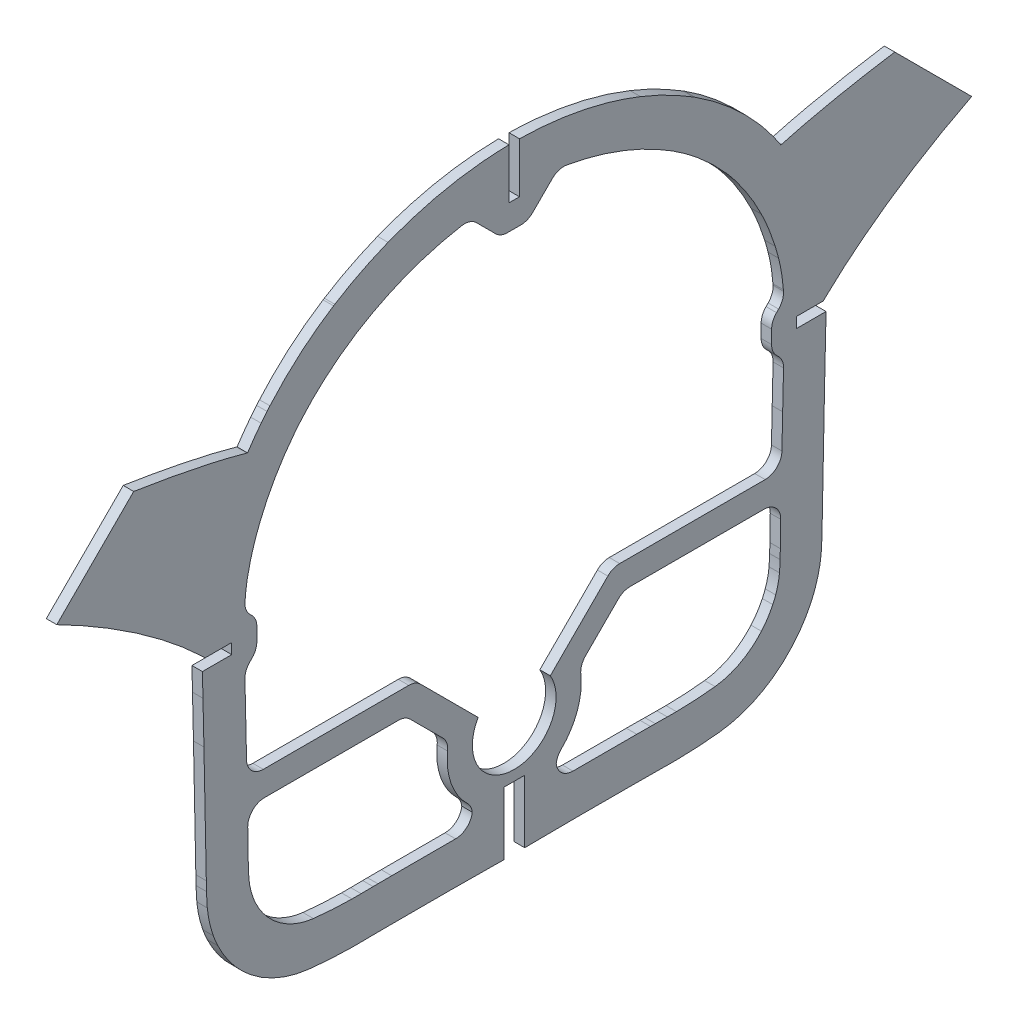
SolidWorks part; units mm, degrees
ref_plane "Front Plane" through (0, 0, 0) normal (0, 0, 1) x (1, 0, 0)
ref_plane "Top Plane" through (0, 0, 0) normal (0, 1, 0) x (1, 0, 0)
ref_plane "Right Plane" through (0, 0, 0) normal (1, 0, 0) x (0, 0, -1)
sketch "Sketch1" plane through (0, 0, 0) normal (1, 0, 0) x (0, 0, -1)
  line L0 (0, 175.0695) -> (0, -175.0695) construction
  line L1 (-81.0819, 60.1686) -> (-80.8925, 60.114)
  line L2 (81.0819, 60.1686) -> (80.8925, 60.114)
  line L3 (-297.6054, 3.4765) -> (-274.8429, 3.4756)
  line L4 (-191.9911, 6.9318) -> (-195.5959, 13.5671)
  line L5 (-198.9428, 3.4765) -> (-204.6569, 9.1906)
  line L6 (-302.2888, 209.9597) -> (-306.2751, 217.2975)
  line L7 (-221.7051, 3.4756) -> (-198.9428, 3.4765)
  line L8 (-221.7051, 3.4756) -> (-222.9696, -1.4236)
  line L9 (-274.8429, 3.4756) -> (-272.4365, -1.5294)
  line L10 (-258.5382, -2.3698) -> (-255.3749, 1.8603)
  line L11 (-274.8429, 3.4756) -> (-283.0321, -0.2624)
  line L12 (-297.6054, 3.4765) -> (-277.6843, 2.1786)
  line L13 (297.6054, 3.4765) -> (277.6843, 2.1786)
  line L14 (274.8429, 3.4756) -> (283.0321, -0.2624)
  line L15 (258.5382, -2.3698) -> (255.3749, 1.8603)
  line L16 (274.8429, 3.4756) -> (272.4365, -1.5294)
  line L17 (221.7051, 3.4756) -> (222.9696, -1.4236)
  line L18 (221.7051, 3.4756) -> (198.9428, 3.4765)
  line L19 (198.9428, 3.4765) -> (204.6569, 9.1906)
  line L20 (191.9911, 6.9318) -> (195.5959, 13.5671)
  line L21 (297.6054, 3.4765) -> (274.8429, 3.4756)
  arc A0 (-54.4352, 85.9349) -> (-54.8089, 85.6993) centre (-15.7197, 24.1221) ccw
  arc A1 (-91.2643, 38.1891) -> (-92.4876, 33.8762) centre (-8.3239, 12.3341) ccw
  arc A2 (-94.6143, 10.7074) -> (-94.6021, 10.1451) centre (33.4905, 13.1911) ccw
  arc A3 (-91.2737, -61.5446) -> (-89.912, -64.8363) centre (-57.9635, -49.6925) ccw
  arc A4 (-41.2731, -85.5527) -> (-42.7128, -85.5618) centre (-34.3065, -1294.7168) ccw
  circle A5 centre (0, 0) radius 12.7
  arc A6 (41.2731, -85.5527) -> (42.7128, -85.5618) centre (34.3065, -1294.7168) cw
  arc A7 (91.2737, -61.5446) -> (89.912, -64.8363) centre (57.9635, -49.6925) cw
  arc A8 (94.6143, 10.7074) -> (94.6021, 10.1451) centre (-33.4905, 13.1911) cw
  arc A9 (91.2643, 38.1891) -> (92.4876, 33.8762) centre (8.3239, 12.3341) cw
  arc A10 (54.4352, 85.9349) -> (54.8089, 85.6993) centre (15.7197, 24.1221) cw
  arc A11 (-274.8429, 3.4756) -> (-221.7051, 3.4756) centre (-248.2741, 72.289) ccw
  arc A12 (274.8429, 3.4756) -> (221.7051, 3.4756) centre (248.2741, 72.289) cw
  spline S0 degree 4 poles (0, 101.4115) (-9.8319, 101.4066) (-19.6573, 100.1828) (-29.2209, 97.7298) (-38.2878, 94.1226) knots 0 0 0 0 0 1 1 1 1 1 weights 1 1 1 1 1
  spline S1 degree 3 poles (-38.2878, 94.1226) (-43.9171, 91.8829) (-49.3269, 89.1344) (-54.4352, 85.9349) knots 0 0 0 0 0.999942 0.999942 0.999942 0.999942 weights 1 1 1 1
  spline S2 degree 3 poles (-54.8089, 85.6993) (-62.0188, 81.1224) (-68.5363, 75.507) (-74.102, 69.0924) knots 0.000118 0.000118 0.000118 0.000118 1 1 1 1 weights 1 1 1 1
  spline S3 degree 3 poles (-74.102, 69.0924) (-74.399, 68.7502) (-74.693, 68.4055) (-74.9844, 68.0586) knots 0 0 0 0 1 1 1 1 weights 1 1 1 1
  spline S4 degree 3 poles (-74.9844, 68.0586) (-75.5924, 67.3349) (-76.1876, 66.6014) (-76.7689, 65.8577) knots 0 0 0 0 1 1 1 1 weights 1 1 1 1
  spline S5 degree 3 poles (-76.7689, 65.8577) (-80.5039, 61.079) (-83.7318, 55.915) (-86.3851, 50.4769) knots 0 0 0 0 1 1 1 1 weights 1 1 1 1
  spline S6 degree 3 poles (-86.3851, 50.4769) (-88.3203, 46.5105) (-89.952, 42.3987) (-91.2643, 38.1891) knots 0 0 0 0 0.976062 0.976062 0.976062 0.976062 weights 1 1 1 1
  spline S7 degree 3 poles (-92.4876, 33.8762) (-93.4352, 30.1741) (-94.0467, 26.3933) (-94.3138, 22.5964) knots 0.000295 0.000295 0.000295 0.000295 1 1 1 1 weights 1 1 1 1
  spline S8 degree 3 poles (-94.3138, 22.5964) (-94.546, 19.2966) (-94.6529, 15.98) (-94.6378, 12.6615) knots 0 0 0 0 1 1 1 1 weights 1 1 1 1
  spline S9 degree 3 poles (-94.6021, 10.1451) (-94.5409, 7.5692) (-94.4811, 4.995) (-94.4219, 2.4225) knots 0.000909 0.000909 0.000909 0.000909 1 1 1 1 weights 1 1 1 1
  spline S10 degree 3 poles (-94.6378, 12.6615) (-94.6349, 12.0102) (-94.6269, 11.3588) (-94.6143, 10.7074) knots 0 0 0 0 1 1 1 1 weights 1 1 1 1
  spline S11 degree 3 poles (-94.4219, 2.4225) (-94.3223, -1.9008) (-94.2213, -6.219) (-94.1228, -10.5326) knots 0 0 0 0 1 1 1 1 weights 1 1 1 1
  spline S12 degree 3 poles (-94.1228, -10.5326) (-93.8522, -22.3825) (-93.5978, -34.207) (-93.404, -46.0282) knots 0 0 0 0 1 1 1 1 weights 1 1 1 1
  spline S13 degree 3 poles (-93.404, -46.0282) (-93.3884, -46.981) (-93.375, -47.934) (-93.3611, -48.887) knots 0 0 0 0 1 1 1 1 weights 1 1 1 1
  spline S14 degree 3 poles (-93.1116, -53.3139) (-92.8366, -56.1171) (-92.219, -58.8878) (-91.2737, -61.5446) knots 0 0 0 0 0.998554 0.998554 0.998554 0.998554 weights 1 1 1 1
  spline S15 degree 3 poles (-93.3611, -48.887) (-93.3396, -50.3606) (-93.2562, -51.8393) (-93.1116, -53.3139) knots 0 0 0 0 1 1 1 1 weights 1 1 1 1
  spline S16 degree 3 poles (-89.912, -64.8363) (-88.5121, -67.7895) (-86.7079, -70.5471) (-84.5693, -73.0032) knots 0.012214 0.012214 0.012214 0.012214 1 1 1 1 weights 1 1 1 1
  spline S17 degree 4 poles (-84.5693, -73.0032) (-80.3112, -77.8934) (-74.8787, -81.7443) (-68.696, -84.0787) (-62.3719, -84.8022) knots 0 0 0 0 0 1 1 1 1 1 weights 1 1 1 1 1
  spline S18 degree 3 poles (-62.3719, -84.8022) (-58.1079, -85.2905) (-53.7407, -85.5613) (-49.3357, -85.605) knots 0 0 0 0 1 1 1 1 weights 1 1 1 1
  spline S19 degree 3 poles (-49.3357, -85.605) (-48.314, -85.6152) (-47.2903, -85.6128) (-46.2655, -85.5987) knots 0 0 0 0 1 1 1 1 weights 1 1 1 1
  spline S20 degree 3 poles (-46.2655, -85.5987) (-45.0812, -85.5825) (-43.8971, -85.5701) (-42.7128, -85.5618) knots 0 0 0 0 1 1 1 1 weights 1 1 1 1
  spline S21 degree 3 poles (-41.2731, -85.5527) (-39.8864, -85.5447) (-38.4993, -85.538) (-37.1118, -85.5314) knots 0.000341 0.000341 0.000341 0.000341 1 1 1 1 weights 1 1 1 1
  spline S22 degree 3 poles (-37.1118, -85.5314) (-24.8076, -85.473) (-12.4473, -85.5107) (0, -85.6893) knots 0 0 0 0 1 1 1 1 weights 1 1 1 1
  spline S23 degree 3 number of poles 90 (-306.2751, 217.2975) -> (-191.9911, 6.9318)
  spline S24 degree 3 poles (-297.6054, 3.4765) (-300.1022, 4.6174) (-302.5664, 5.8477) (-306.2126, 7.8305) (-307.4217, 8.5157) (-309.8066, 9.9227) (-310.9836, 10.645) (-316.7923, 14.3501) (-321.1964, 17.6107) (-329.5298, 24.712) (-333.4591, 28.5526) (-338.0635, 33.7287) (-338.9683, 34.7823) (-340.7331, 36.9106) (-341.5949, 37.9874) (-344.1191, 41.2552) (-345.7206, 43.4835) (-350.2851, 50.3152) (-353.0092, 55.0648) (-356.6122, 62.4848) (-357.7324, 65.0076) (-359.8068, 70.1546) (-360.7499, 72.7517) (-363.3001, 80.5988) (-364.6313, 85.91) (-366.0828, 93.995) (-366.4754, 96.7098) (-366.9256, 100.812) (-367.0525, 102.1844) (-367.2595, 104.9394) (-367.3396, 106.3238) (-367.6202, 113.2511) (-367.4614, 118.7454) (-366.4066, 129.6428) (-365.5106, 135.0458) (-363.9214, 141.7414) (-363.58, 143.0776) (-362.8495, 145.7441) (-362.4595, 147.077) (-361.2235, 151.0452) (-360.3128, 153.6476) (-357.327, 161.3289) (-354.9994, 166.2824) (-351.006, 173.4633) (-349.591, 175.8153) (-347.3402, 179.2795) (-346.5686, 180.4237) (-344.982, 182.6904) (-344.1654, 183.8149) (-340.0019, 189.3445) (-336.4015, 193.4909) (-328.6795, 201.2473) (-324.5578, 204.8572) (-319.072, 209.0262) (-317.958, 209.8428) (-315.6961, 211.4409) (-314.5477, 212.2227) (-311.068, 214.5034) (-308.6972, 215.9417) (-306.2751, 217.2975) knots 0 0 0 0 0.03125 0.03125 0.046875 0.046875 0.0625 0.0625 0.125 0.125 0.1875 0.1875 0.203125 0.203125 0.21875 0.21875 0.25 0.25 0.3125 0.3125 0.34375 0.34375 0.375 0.375 0.4375 0.4375 0.46875 0.46875 0.484375 0.484375 0.5 0.5 0.5625 0.5625 0.625 0.625 0.640625 0.640625 0.65625 0.65625 0.6875 0.6875 0.75 0.75 0.78125 0.78125 0.796875 0.796875 0.8125 0.8125 0.875 0.875 0.9375 0.9375 0.953125 0.953125 0.96875 0.96875 1 1 1 1
  spline S25 degree 3 poles (-191.9911, 6.9318) (-194.2811, 5.6993) (-196.5985, 4.5482) (-198.9428, 3.4765) knots 0 0 0 0 0.995619 0.995619 0.995619 0.995619
  spline S26 degree 3 number of poles 88 (-302.2888, 209.9597) -> (-195.5959, 13.5671)
  spline S27 degree 3 poles (-221.7051, 3.4756) (-222.2274, 3.3481) (-222.7518, 3.2456) (-223.8266, 3.0586) (-224.3771, 2.9761) (-226.0307, 2.7526) (-227.1356, 2.6348) (-230.4544, 2.3296) (-232.6722, 2.1907) (-237.1131, 1.9763) (-239.3363, 1.9031) (-243.7868, 1.8061) (-246.012, 1.7826) (-250.462, 1.7811) (-252.687, 1.8031) (-257.1365, 1.8971) (-259.3619, 1.9689) (-263.8053, 2.1805) (-266.0241, 2.318) (-269.3433, 2.621) (-270.4482, 2.7381) (-272.1012, 2.9606) (-272.6515, 3.0426) (-273.7496, 3.233) (-274.2975, 3.3404) (-274.8429, 3.4756) knots 0.001374 0.001374 0.001374 0.001374 0.03125 0.03125 0.0625 0.0625 0.125 0.125 0.25 0.25 0.375 0.375 0.5 0.5 0.625 0.625 0.75 0.75 0.875 0.875 0.9375 0.9375 0.96875 0.96875 0.999998 0.999998 0.999998 0.999998
  spline S28 degree 3 poles (-274.8429, 3.4756) (-280.2539, 4.8127) (-285.5214, 6.5451) (-293.2106, 9.7277) (-295.7382, 10.8862) (-299.4755, 12.7733) (-300.7122, 13.4272) (-303.1672, 14.7855) (-304.3849, 15.4897) (-310.3757, 19.1071) (-314.8997, 22.33) (-323.4277, 29.4129) (-327.4317, 33.2729) (-332.0999, 38.5104) (-333.0155, 39.5775) (-334.7976, 41.7353) (-335.666, 42.8281) (-338.2045, 46.1475) (-339.8078, 48.4151) (-344.3545, 55.3793) (-347.0364, 60.2365) (-349.944, 66.581) (-350.5031, 67.8636) (-351.576, 70.4567) (-352.089, 71.7658) (-353.5474, 75.702) (-354.4165, 78.3487) (-356.7219, 86.3545) (-357.8577, 91.7792) (-358.9583, 100.0477) (-359.2242, 102.8259) (-359.4675, 107.0271) (-359.5225, 108.4325) (-359.5797, 111.231) (-359.5821, 112.627) (-359.4651, 119.5914) (-358.9605, 125.1126) (-357.5953, 133.3199) (-357.0385, 136.0432) (-356.0476, 140.109) (-355.6914, 141.4612) (-354.9263, 144.1589) (-354.517, 145.5053) (-352.3558, 152.164) (-350.2495, 157.3042) (-345.3048, 167.2224) (-342.4665, 172.0003) (-338.4438, 177.7378) (-337.6142, 178.8749) (-335.9207, 181.1068) (-335.0553, 182.2037) (-332.4044, 185.4379) (-330.564, 187.519) (-324.8265, 193.5406) (-320.7146, 197.2606) (-315.2092, 201.5355) (-314.0897, 202.3716) (-311.8134, 204.0055) (-310.6553, 204.8042) (-307.1418, 207.1299) (-304.7434, 208.5901) (-302.2888, 209.9597) knots 0 0 0 0 0.0625 0.0625 0.09375 0.09375 0.109375 0.109375 0.125 0.125 0.1875 0.1875 0.25 0.25 0.265625 0.265625 0.28125 0.28125 0.3125 0.3125 0.375 0.375 0.390625 0.390625 0.40625 0.40625 0.4375 0.4375 0.5 0.5 0.53125 0.53125 0.546875 0.546875 0.5625 0.5625 0.625 0.625 0.65625 0.65625 0.671875 0.671875 0.6875 0.6875 0.75 0.75 0.8125 0.8125 0.828125 0.828125 0.84375 0.84375 0.875 0.875 0.9375 0.9375 0.953125 0.953125 0.96875 0.96875 1 1 1 1
  spline S29 degree 3 poles (-195.5959, 13.5671) (-199.7559, 11.32) (-204.0137, 9.3617) (-212.7177, 6.0006) (-217.1639, 4.5979) (-221.7051, 3.4756) knots 0 0 0 0 0.5 0.5 1 1 1 1
  spline S30 degree 3 poles (-146.5731, 71.1593) (-141.0597, 70.6098) (-135.5516, 69.9964) (-124.5571, 68.6107) (-119.0712, 67.8388) (-108.1284, 66.0937) (-102.6705, 65.1218) (-94.5318, 63.461) (-91.8263, 62.8737) (-87.783, 61.9241) (-86.4377, 61.5961) (-83.7538, 60.9098) (-82.4149, 60.5527) (-81.0819, 60.1686) knots 0 0 0 0 0.25 0.25 0.5 0.5 0.75 0.75 0.875 0.875 0.9375 0.9375 1 1 1 1
  spline S31 degree 3 poles (-81.0819, -2.8592) (-82.1374, -1.0384) (-83.3128, 0.6836) (-85.804, 4.0118) (-87.1225, 5.6156) (-89.8691, 8.733) (-91.2969, 10.2467) (-94.2399, 13.2019) (-95.757, 14.6441) (-100.381, 18.8412) (-103.5732, 21.4824) (-110.129, 26.5196) (-113.4933, 28.9142) (-120.3703, 33.4913) (-123.8832, 35.6733) (-129.2532, 38.802) (-131.0601, 39.8208) (-134.706, 41.8122) (-136.5465, 42.7856) (-145.8029, 47.529) (-153.3842, 50.9348) (-161.1121, 54.0168) knots 0 0 0 0 0.0625 0.0625 0.125 0.125 0.1875 0.1875 0.25 0.25 0.375 0.375 0.5 0.5 0.625 0.625 0.6875 0.6875 0.75 0.75 1 1 1 1
  spline S32 degree 3 poles (-297.6054, 3.4765) (-296.6449, 3.037) (-295.6656, 2.672) (-293.6879, 2.0184) (-292.6891, 1.7315) (-289.6731, 0.9482) (-287.6371, 0.5273) (-283.537, -0.2025) (-281.4699, -0.5094) (-277.3363, -1.0412) (-275.2674, -1.266) (-269.056, -1.8468) (-264.9089, -2.1109) (-256.6057, -2.4596) (-252.4495, -2.5429) (-244.1286, -2.5433) (-239.9597, -2.4601) (-231.6451, -2.1113) (-227.4973, -1.8471) (-221.2947, -1.2674) (-219.2304, -1.0433) (-215.1103, -0.5139) (-213.0545, -0.2093) (-209.98, 0.3366) (-208.9568, 0.5336) (-206.9144, 0.9668) (-205.8935, 1.2034) (-203.867, 1.7292) (-202.8622, 2.0177) (-200.8783, 2.6735) (-199.8988, 3.0391) (-198.9428, 3.4765) knots 0 0 0 0 0.03125 0.03125 0.0625 0.0625 0.125 0.125 0.1875 0.1875 0.25 0.25 0.375 0.375 0.5 0.5 0.625 0.625 0.75 0.75 0.8125 0.8125 0.875 0.875 0.90625 0.90625 0.9375 0.9375 0.96875 0.96875 1 1 1 1
  spline S33 degree 3 poles (297.6054, 3.4765) (296.6449, 3.037) (295.6656, 2.672) (293.6879, 2.0184) (292.6891, 1.7315) (289.6731, 0.9482) (287.6371, 0.5273) (283.537, -0.2025) (281.4699, -0.5094) (277.3363, -1.0412) (275.2674, -1.266) (269.056, -1.8468) (264.9089, -2.1109) (256.6057, -2.4596) (252.4495, -2.5429) (244.1286, -2.5433) (239.9597, -2.4601) (231.6451, -2.1113) (227.4973, -1.8471) (221.2947, -1.2674) (219.2304, -1.0433) (215.1103, -0.5139) (213.0545, -0.2093) (209.98, 0.3366) (208.9568, 0.5336) (206.9144, 0.9668) (205.8935, 1.2034) (203.867, 1.7292) (202.8622, 2.0177) (200.8783, 2.6735) (199.8988, 3.0391) (198.9428, 3.4765) knots 0 0 0 0 0.03125 0.03125 0.0625 0.0625 0.125 0.125 0.1875 0.1875 0.25 0.25 0.375 0.375 0.5 0.5 0.625 0.625 0.75 0.75 0.8125 0.8125 0.875 0.875 0.90625 0.90625 0.9375 0.9375 0.96875 0.96875 1 1 1 1
  spline S34 degree 3 poles (81.0819, -2.8592) (82.1374, -1.0384) (83.3128, 0.6836) (85.804, 4.0118) (87.1225, 5.6156) (89.8691, 8.733) (91.2969, 10.2467) (94.2399, 13.2019) (95.757, 14.6441) (100.381, 18.8412) (103.5732, 21.4824) (110.129, 26.5196) (113.4933, 28.9142) (120.3703, 33.4913) (123.8832, 35.6733) (129.2532, 38.802) (131.0601, 39.8208) (134.706, 41.8122) (136.5465, 42.7856) (145.8029, 47.529) (153.3842, 50.9348) (161.1121, 54.0168) knots 0 0 0 0 0.0625 0.0625 0.125 0.125 0.1875 0.1875 0.25 0.25 0.375 0.375 0.5 0.5 0.625 0.625 0.6875 0.6875 0.75 0.75 1 1 1 1
  spline S35 degree 3 poles (146.5731, 71.1593) (141.0597, 70.6098) (135.5516, 69.9964) (124.5571, 68.6107) (119.0712, 67.8388) (108.1284, 66.0937) (102.6705, 65.1218) (94.5318, 63.461) (91.8263, 62.8737) (87.783, 61.9241) (86.4377, 61.5961) (83.7538, 60.9098) (82.4149, 60.5527) (81.0819, 60.1686) knots 0 0 0 0 0.25 0.25 0.5 0.5 0.75 0.75 0.875 0.875 0.9375 0.9375 1 1 1 1
  spline S36 degree 3 poles (195.5959, 13.5671) (199.7559, 11.32) (204.0137, 9.3617) (212.7177, 6.0006) (217.1639, 4.5979) (221.7051, 3.4756) knots 0 0 0 0 0.5 0.5 1 1 1 1
  spline S37 degree 3 poles (274.8429, 3.4756) (280.2539, 4.8127) (285.5214, 6.5451) (293.2106, 9.7277) (295.7382, 10.8862) (299.4755, 12.7733) (300.7122, 13.4272) (303.1672, 14.7855) (304.3849, 15.4897) (310.3757, 19.1071) (314.8997, 22.33) (323.4277, 29.4129) (327.4317, 33.2729) (332.0999, 38.5104) (333.0155, 39.5775) (334.7976, 41.7353) (335.666, 42.8281) (338.2045, 46.1475) (339.8078, 48.4151) (344.3545, 55.3793) (347.0364, 60.2365) (349.944, 66.581) (350.5031, 67.8636) (351.576, 70.4567) (352.089, 71.7658) (353.5474, 75.702) (354.4165, 78.3487) (356.7219, 86.3545) (357.8577, 91.7792) (358.9583, 100.0477) (359.2242, 102.8259) (359.4675, 107.0271) (359.5225, 108.4325) (359.5797, 111.231) (359.5821, 112.627) (359.4651, 119.5914) (358.9605, 125.1126) (357.5953, 133.3199) (357.0385, 136.0432) (356.0476, 140.109) (355.6914, 141.4612) (354.9263, 144.1589) (354.517, 145.5053) (352.3558, 152.164) (350.2495, 157.3042) (345.3048, 167.2224) (342.4665, 172.0003) (338.4438, 177.7378) (337.6142, 178.8749) (335.9207, 181.1068) (335.0553, 182.2037) (332.4044, 185.4379) (330.564, 187.519) (324.8265, 193.5406) (320.7146, 197.2606) (315.2092, 201.5355) (314.0897, 202.3716) (311.8134, 204.0055) (310.6553, 204.8042) (307.1418, 207.1299) (304.7434, 208.5901) (302.2888, 209.9597) knots 0 0 0 0 0.0625 0.0625 0.09375 0.09375 0.109375 0.109375 0.125 0.125 0.1875 0.1875 0.25 0.25 0.265625 0.265625 0.28125 0.28125 0.3125 0.3125 0.375 0.375 0.390625 0.390625 0.40625 0.40625 0.4375 0.4375 0.5 0.5 0.53125 0.53125 0.546875 0.546875 0.5625 0.5625 0.625 0.625 0.65625 0.65625 0.671875 0.671875 0.6875 0.6875 0.75 0.75 0.8125 0.8125 0.828125 0.828125 0.84375 0.84375 0.875 0.875 0.9375 0.9375 0.953125 0.953125 0.96875 0.96875 1 1 1 1
  spline S38 degree 3 poles (221.7051, 3.4756) (222.2274, 3.3481) (222.7518, 3.2456) (223.8266, 3.0586) (224.3771, 2.9761) (226.0307, 2.7526) (227.1356, 2.6348) (230.4544, 2.3296) (232.6722, 2.1907) (237.1131, 1.9763) (239.3363, 1.9031) (243.7868, 1.8061) (246.012, 1.7826) (250.462, 1.7811) (252.687, 1.8031) (257.1365, 1.8971) (259.3619, 1.9689) (263.8053, 2.1805) (266.0241, 2.318) (269.3433, 2.621) (270.4482, 2.7381) (272.1012, 2.9606) (272.6515, 3.0426) (273.7496, 3.233) (274.2975, 3.3404) (274.8429, 3.4756) knots 0.001374 0.001374 0.001374 0.001374 0.03125 0.03125 0.0625 0.0625 0.125 0.125 0.25 0.25 0.375 0.375 0.5 0.5 0.625 0.625 0.75 0.75 0.875 0.875 0.9375 0.9375 0.96875 0.96875 0.999998 0.999998 0.999998 0.999998
  spline S39 degree 3 number of poles 88 (302.2888, 209.9597) -> (195.5959, 13.5671)
  spline S40 degree 3 poles (191.9911, 6.9318) (194.2811, 5.6993) (196.5985, 4.5482) (198.9428, 3.4765) knots 0 0 0 0 0.995619 0.995619 0.995619 0.995619
  spline S41 degree 3 poles (297.6054, 3.4765) (300.1022, 4.6174) (302.5664, 5.8477) (306.2126, 7.8305) (307.4217, 8.5157) (309.8066, 9.9227) (310.9836, 10.645) (316.7923, 14.3501) (321.1964, 17.6107) (329.5298, 24.712) (333.4591, 28.5526) (338.0635, 33.7287) (338.9683, 34.7823) (340.7331, 36.9106) (341.5949, 37.9874) (344.1191, 41.2552) (345.7206, 43.4835) (350.2851, 50.3152) (353.0092, 55.0648) (356.6122, 62.4848) (357.7324, 65.0076) (359.8068, 70.1546) (360.7499, 72.7517) (363.3001, 80.5988) (364.6313, 85.91) (366.0828, 93.995) (366.4754, 96.7098) (366.9256, 100.812) (367.0525, 102.1844) (367.2595, 104.9394) (367.3396, 106.3238) (367.6202, 113.2511) (367.4614, 118.7454) (366.4066, 129.6428) (365.5106, 135.0458) (363.9214, 141.7414) (363.58, 143.0776) (362.8495, 145.7441) (362.4595, 147.077) (361.2235, 151.0452) (360.3128, 153.6476) (357.327, 161.3289) (354.9994, 166.2824) (351.006, 173.4633) (349.591, 175.8153) (347.3402, 179.2795) (346.5686, 180.4237) (344.982, 182.6904) (344.1654, 183.8149) (340.0019, 189.3445) (336.4015, 193.4909) (328.6795, 201.2473) (324.5578, 204.8572) (319.072, 209.0262) (317.958, 209.8428) (315.6961, 211.4409) (314.5477, 212.2227) (311.068, 214.5034) (308.6972, 215.9417) (306.2751, 217.2975) knots 0 0 0 0 0.03125 0.03125 0.046875 0.046875 0.0625 0.0625 0.125 0.125 0.1875 0.1875 0.203125 0.203125 0.21875 0.21875 0.25 0.25 0.3125 0.3125 0.34375 0.34375 0.375 0.375 0.4375 0.4375 0.46875 0.46875 0.484375 0.484375 0.5 0.5 0.5625 0.5625 0.625 0.625 0.640625 0.640625 0.65625 0.65625 0.6875 0.6875 0.75 0.75 0.78125 0.78125 0.796875 0.796875 0.8125 0.8125 0.875 0.875 0.9375 0.9375 0.953125 0.953125 0.96875 0.96875 1 1 1 1
  spline S42 degree 3 number of poles 90 (306.2751, 217.2975) -> (191.9911, 6.9318)
  spline S43 degree 3 poles (37.1118, -85.5314) (24.8076, -85.473) (12.4473, -85.5107) (0, -85.6893) knots 0 0 0 0 1 1 1 1 weights 1 1 1 1
  spline S44 degree 3 poles (41.2731, -85.5527) (39.8864, -85.5447) (38.4993, -85.538) (37.1118, -85.5314) knots 0.000341 0.000341 0.000341 0.000341 1 1 1 1 weights 1 1 1 1
  spline S45 degree 3 poles (46.2655, -85.5987) (45.0812, -85.5825) (43.8971, -85.5701) (42.7128, -85.5618) knots 0 0 0 0 1 1 1 1 weights 1 1 1 1
  spline S46 degree 3 poles (49.3357, -85.605) (48.314, -85.6152) (47.2903, -85.6128) (46.2655, -85.5987) knots 0 0 0 0 1 1 1 1 weights 1 1 1 1
  spline S47 degree 3 poles (62.3719, -84.8022) (58.1079, -85.2905) (53.7407, -85.5613) (49.3357, -85.605) knots 0 0 0 0 1 1 1 1 weights 1 1 1 1
  spline S48 degree 4 poles (84.5693, -73.0032) (80.3112, -77.8934) (74.8787, -81.7443) (68.696, -84.0787) (62.3719, -84.8022) knots 0 0 0 0 0 1 1 1 1 1 weights 1 1 1 1 1
  spline S49 degree 3 poles (89.912, -64.8363) (88.5121, -67.7895) (86.7079, -70.5471) (84.5693, -73.0032) knots 0.012214 0.012214 0.012214 0.012214 1 1 1 1 weights 1 1 1 1
  spline S50 degree 3 poles (93.3611, -48.887) (93.3396, -50.3606) (93.2562, -51.8393) (93.1116, -53.3139) knots 0 0 0 0 1 1 1 1 weights 1 1 1 1
  spline S51 degree 3 poles (93.1116, -53.3139) (92.8366, -56.1171) (92.219, -58.8878) (91.2737, -61.5446) knots 0 0 0 0 0.998554 0.998554 0.998554 0.998554 weights 1 1 1 1
  spline S52 degree 3 poles (93.404, -46.0282) (93.3884, -46.981) (93.375, -47.934) (93.3611, -48.887) knots 0 0 0 0 1 1 1 1 weights 1 1 1 1
  spline S53 degree 3 poles (94.1228, -10.5326) (93.8522, -22.3825) (93.5978, -34.207) (93.404, -46.0282) knots 0 0 0 0 1 1 1 1 weights 1 1 1 1
  spline S54 degree 3 poles (94.4219, 2.4225) (94.3223, -1.9008) (94.2213, -6.219) (94.1228, -10.5326) knots 0 0 0 0 1 1 1 1 weights 1 1 1 1
  spline S55 degree 3 poles (94.6378, 12.6615) (94.6349, 12.0102) (94.6269, 11.3588) (94.6143, 10.7074) knots 0 0 0 0 1 1 1 1 weights 1 1 1 1
  spline S56 degree 3 poles (94.6021, 10.1451) (94.5409, 7.5692) (94.4811, 4.995) (94.4219, 2.4225) knots 0.000909 0.000909 0.000909 0.000909 1 1 1 1 weights 1 1 1 1
  spline S57 degree 3 poles (94.3138, 22.5964) (94.546, 19.2966) (94.6529, 15.98) (94.6378, 12.6615) knots 0 0 0 0 1 1 1 1 weights 1 1 1 1
  spline S58 degree 3 poles (92.4876, 33.8762) (93.4352, 30.1741) (94.0467, 26.3933) (94.3138, 22.5964) knots 0.000295 0.000295 0.000295 0.000295 1 1 1 1 weights 1 1 1 1
  spline S59 degree 3 poles (86.3851, 50.4769) (88.3203, 46.5105) (89.952, 42.3987) (91.2643, 38.1891) knots 0 0 0 0 0.976062 0.976062 0.976062 0.976062 weights 1 1 1 1
  spline S60 degree 3 poles (76.7689, 65.8577) (80.5039, 61.079) (83.7318, 55.915) (86.3851, 50.4769) knots 0 0 0 0 1 1 1 1 weights 1 1 1 1
  spline S61 degree 3 poles (74.9844, 68.0586) (75.5924, 67.3349) (76.1876, 66.6014) (76.7689, 65.8577) knots 0 0 0 0 1 1 1 1 weights 1 1 1 1
  spline S62 degree 3 poles (74.102, 69.0924) (74.399, 68.7502) (74.693, 68.4055) (74.9844, 68.0586) knots 0 0 0 0 1 1 1 1 weights 1 1 1 1
  spline S63 degree 3 poles (54.8089, 85.6993) (62.0188, 81.1224) (68.5363, 75.507) (74.102, 69.0924) knots 0.000118 0.000118 0.000118 0.000118 1 1 1 1 weights 1 1 1 1
  spline S64 degree 3 poles (38.2878, 94.1226) (43.9171, 91.8829) (49.3269, 89.1344) (54.4352, 85.9349) knots 0 0 0 0 0.999942 0.999942 0.999942 0.999942 weights 1 1 1 1
  spline S65 degree 4 poles (0, 101.4115) (9.8319, 101.4066) (19.6573, 100.1828) (29.2209, 97.7298) (38.2878, 94.1226) knots 0 0 0 0 0 1 1 1 1 1 weights 1 1 1 1 1
  point P109 (-248.274, -1.4754)
  point P113 (248.274, -1.4754)
  dimension "D1" = 25.4
extrude "Boss-Extrude1" add sketch "Sketch1" along normal mid plane 3.175 contours S65 S0 S1 A0 S2 S3 S4 S5 S6 A1 S7 S8 S10 A2 S9 S11 S12 S13 S15 S14 A3 S16 S17 S18 S19 S20 A4 S21 S22 S43 S44 A6 S45 S46 S47 S48 S49 A7 S51 S50 S52 S53 S54 S56 A8 S55 S57 | S31 S8 S7 A1 S6 S5 L1 S30 S23 | S31 S23 S30 S26 | L2 S60 S59 A9 S58 S57 S34 S42 S35 | S35 S42 S34 S39 | S26 S30 S23 L6 | L3 S28 L6 S24 | S23 S31 S26 | S29 S25 | L5 S29 L7 | L8 S32 L7 | L10 S32 L8 A11 | A11 S27 L10 | L10 S27 A11 | L9 S32 L10 A11 | L11 S32 L9 | L3 L12 L11 | L12 S32 L11 | S34 S42 L20 S39 | S41 S42 S35 S39 S37 L21 | L20 S40 L19 S36 | S36 L19 L18 | S33 L17 L18 | S33 L15 A12 L17 | S38 A12 L15 | S38 L15 A12 | S33 L16 A12 L15 | S33 L14 L16 | L13 L21 L14 | S33 L13 L14 region at (0, 48.2732, 112.8454) region at (0, 61.4757, 76.7272) region at (0, 72.947, 140.5235) region at (0, 60.0242, 145.5817) region at (0, 212.5162, 306.3296) region at (0, 28.2588, 170.7212) region at (0, 3.0436, 283.3775) region at (0, 1.7592, 286.7911) region at (0, 8.37, 197.8678) region at (0, -0.2902, 267.1572) region at (0, 0.5263, 276.7954) region at (0, 1.1896, 262.7348) region at (0, 5.3222, 208.0956) region at (0, 1.6414, 213.6095) region at (0, -0.8156, 235.5909) region at (0, 0.5579, 242.9465) region at (0, 48.2731, -112.8454) region at (0, 200.6107, -172.3031) region at (0, 60.0242, -145.5817) region at (0, 28.2587, -170.7212) region at (0, 1.7592, -286.7911) region at (0, 3.0436, -283.3775) region at (0, 8.37, -197.8678) region at (0, 0.5263, -276.7954) region at (0, -0.2902, -267.1572) region at (0, 1.1896, -262.7348) region at (0, 5.3222, -208.0956) region at (0, 1.6414, -213.6095) region at (0, 0.5579, -242.9464) region at (0, -0.8156, -235.5909)
sketch "Sketch3" plane through (1.5875, 0, 0) normal (1, 0, 0) x (0, 0, -1)
  line L0 (-81.0819, 60.1686) -> (-80.8925, 60.114)
  line L1 (81.0819, 60.1686) -> (80.8925, 60.114)
  line L2 (-77.5653, 72.372) -> (-77.376, 72.3174)
  line L3 (84.5984, 47.9651) -> (84.4091, 47.9106)
  arc A0 (-54.4352, 85.9349) -> (-54.8089, 85.6993) centre (-15.7197, 24.1221) ccw
  arc A1 (-91.2643, 38.1891) -> (-92.4876, 33.8762) centre (-8.3239, 12.3341) ccw
  arc A2 (-94.6143, 10.7074) -> (-94.6021, 10.1451) centre (33.4905, 13.1911) ccw
  arc A3 (-91.2737, -61.5446) -> (-89.912, -64.8363) centre (-57.9635, -49.6925) ccw
  arc A4 (-41.2731, -85.5527) -> (-42.7128, -85.5618) centre (-34.3065, -1294.7168) ccw
  circle A5 centre (0, 0) radius 12.7
  arc A6 (41.2731, -85.5527) -> (42.7128, -85.5618) centre (34.3065, -1294.7168) cw
  arc A7 (91.2737, -61.5446) -> (89.912, -64.8363) centre (57.9635, -49.6925) cw
  arc A8 (94.6143, 10.7074) -> (94.6021, 10.1451) centre (-33.4905, 13.1911) cw
  arc A9 (91.2643, 38.1891) -> (92.4876, 33.8762) centre (8.3239, 12.3341) cw
  arc A10 (54.4352, 85.9349) -> (54.8089, 85.6993) centre (15.7197, 24.1221) cw
  arc A11 (-47.6939, 75.1718) -> (-48.0025, 74.9772) centre (-15.7197, 24.1221) ccw
  arc A12 (-79.1397, 34.4095) -> (-80.1842, 30.727) centre (-8.3239, 12.3341) ccw
  arc A13 (-81.9167, 10.9539) -> (-81.9057, 10.447) centre (33.4905, 13.191) ccw
  arc A14 (-79.3085, -57.2873) -> (-78.4359, -59.3966) centre (-57.9635, -49.6925) ccw
  arc A15 (-41.3463, -72.8529) -> (-42.8011, -72.8621) centre (-34.3065, -1294.7168) ccw
  arc A16 (41.3463, -72.8529) -> (42.8011, -72.8621) centre (34.3065, -1294.7168) cw
  arc A17 (79.3085, -57.2873) -> (78.4359, -59.3966) centre (57.9635, -49.6925) cw
  arc A18 (81.9167, 10.9539) -> (81.9057, 10.447) centre (-33.4905, 13.191) cw
  arc A19 (79.1397, 34.4095) -> (80.1842, 30.727) centre (8.3239, 12.3341) cw
  arc A20 (47.6939, 75.1718) -> (48.0025, 74.9772) centre (15.7197, 24.1221) cw
  circle A21 centre (0, 0) radius 20.32
  spline S0 degree 4 poles (0, 101.4115) (-9.8319, 101.4066) (-19.6573, 100.1828) (-29.2209, 97.7298) (-38.2878, 94.1226) knots 0 0 0 0 0 1 1 1 1 1 weights 1 1 1 1 1
  spline S1 degree 3 poles (-38.2878, 94.1226) (-43.9171, 91.8829) (-49.3269, 89.1344) (-54.4352, 85.9349) knots 0 0 0 0 0.999942 0.999942 0.999942 0.999942 weights 1 1 1 1
  spline S2 degree 3 poles (-54.8089, 85.6993) (-62.0188, 81.1224) (-68.5363, 75.507) (-74.102, 69.0925) knots 0.000118 0.000118 0.000118 0.000118 1 1 1 1 weights 1 1 1 1
  spline S3 degree 3 poles (-74.102, 69.0925) (-74.399, 68.7502) (-74.693, 68.4055) (-74.9844, 68.0586) knots 0 0 0 0 1 1 1 1 weights 1 1 1 1
  spline S4 degree 3 poles (-74.9844, 68.0586) (-75.5924, 67.335) (-76.1876, 66.6014) (-76.7689, 65.8577) knots 0 0 0 0 1 1 1 1 weights 1 1 1 1
  spline S5 degree 3 poles (-76.7689, 65.8577) (-80.5039, 61.079) (-83.7318, 55.915) (-86.3851, 50.4769) knots 0 0 0 0 1 1 1 1 weights 1 1 1 1
  spline S6 degree 3 poles (-86.3851, 50.4769) (-88.3203, 46.5105) (-89.952, 42.3987) (-91.2643, 38.1891) knots 0 0 0 0 0.976062 0.976062 0.976062 0.976062 weights 1 1 1 1
  spline S7 degree 3 poles (-92.4876, 33.8762) (-93.4352, 30.1741) (-94.0467, 26.3933) (-94.3138, 22.5964) knots 0.000295 0.000295 0.000295 0.000295 1 1 1 1 weights 1 1 1 1
  spline S8 degree 3 poles (-94.3138, 22.5964) (-94.546, 19.2966) (-94.6529, 15.98) (-94.6378, 12.6615) knots 0 0 0 0 1 1 1 1 weights 1 1 1 1
  spline S9 degree 3 poles (-94.6021, 10.1451) (-94.5409, 7.5692) (-94.4811, 4.995) (-94.4219, 2.4225) knots 0.000909 0.000909 0.000909 0.000909 1 1 1 1 weights 1 1 1 1
  spline S10 degree 3 poles (-94.6378, 12.6615) (-94.6349, 12.0102) (-94.6269, 11.3588) (-94.6143, 10.7074) knots 0 0 0 0 1 1 1 1 weights 1 1 1 1
  spline S11 degree 3 poles (-94.4219, 2.4225) (-94.3223, -1.9008) (-94.2213, -6.219) (-94.1228, -10.5326) knots 0 0 0 0 1 1 1 1 weights 1 1 1 1
  spline S12 degree 3 poles (-94.1228, -10.5326) (-93.8522, -22.3825) (-93.5978, -34.207) (-93.404, -46.0282) knots 0 0 0 0 1 1 1 1 weights 1 1 1 1
  spline S13 degree 3 poles (-93.404, -46.0282) (-93.3884, -46.981) (-93.375, -47.934) (-93.3611, -48.887) knots 0 0 0 0 1 1 1 1 weights 1 1 1 1
  spline S14 degree 3 poles (-93.1116, -53.3139) (-92.8366, -56.1171) (-92.219, -58.8878) (-91.2737, -61.5446) knots 0 0 0 0 0.998554 0.998554 0.998554 0.998554 weights 1 1 1 1
  spline S15 degree 3 poles (-93.3611, -48.887) (-93.3396, -50.3606) (-93.2562, -51.8393) (-93.1116, -53.3139) knots 0 0 0 0 1 1 1 1 weights 1 1 1 1
  spline S16 degree 3 poles (-89.912, -64.8363) (-88.5121, -67.7895) (-86.7079, -70.5471) (-84.5693, -73.0032) knots 0.012214 0.012214 0.012214 0.012214 1 1 1 1 weights 1 1 1 1
  spline S17 degree 4 poles (-84.5693, -73.0032) (-80.3112, -77.8934) (-74.8787, -81.7443) (-68.696, -84.0787) (-62.3719, -84.8022) knots 0 0 0 0 0 1 1 1 1 1 weights 1 1 1 1 1
  spline S18 degree 3 poles (-62.3719, -84.8022) (-58.1079, -85.2905) (-53.7407, -85.5613) (-49.3357, -85.605) knots 0 0 0 0 1 1 1 1 weights 1 1 1 1
  spline S19 degree 3 poles (-49.3357, -85.605) (-48.314, -85.6152) (-47.2903, -85.6128) (-46.2655, -85.5987) knots 0 0 0 0 1 1 1 1 weights 1 1 1 1
  spline S20 degree 3 poles (-46.2655, -85.5987) (-45.0812, -85.5825) (-43.8971, -85.5701) (-42.7128, -85.5618) knots 0 0 0 0 1 1 1 1 weights 1 1 1 1
  spline S21 degree 3 poles (-41.2731, -85.5527) (-39.8864, -85.5447) (-38.4993, -85.538) (-37.1118, -85.5314) knots 0.000341 0.000341 0.000341 0.000341 1 1 1 1 weights 1 1 1 1
  spline S22 degree 3 poles (-37.1118, -85.5314) (-24.8076, -85.473) (-12.4473, -85.5107) (0, -85.6893) knots 0 0 0 0 1 1 1 1 weights 1 1 1 1
  spline S43 degree 3 poles (37.1118, -85.5314) (24.8076, -85.473) (12.4473, -85.5107) (0, -85.6893) knots 0 0 0 0 1 1 1 1 weights 1 1 1 1
  spline S44 degree 3 poles (41.2731, -85.5527) (39.8864, -85.5447) (38.4993, -85.538) (37.1118, -85.5314) knots 0.000341 0.000341 0.000341 0.000341 1 1 1 1 weights 1 1 1 1
  spline S45 degree 3 poles (46.2655, -85.5987) (45.0812, -85.5825) (43.8971, -85.5701) (42.7128, -85.5618) knots 0 0 0 0 1 1 1 1 weights 1 1 1 1
  spline S46 degree 3 poles (49.3357, -85.605) (48.314, -85.6152) (47.2903, -85.6128) (46.2655, -85.5987) knots 0 0 0 0 1 1 1 1 weights 1 1 1 1
  spline S47 degree 3 poles (62.3719, -84.8022) (58.1079, -85.2905) (53.7407, -85.5613) (49.3357, -85.605) knots 0 0 0 0 1 1 1 1 weights 1 1 1 1
  spline S48 degree 4 poles (84.5693, -73.0032) (80.3112, -77.8934) (74.8787, -81.7443) (68.696, -84.0787) (62.3719, -84.8022) knots 0 0 0 0 0 1 1 1 1 1 weights 1 1 1 1 1
  spline S49 degree 3 poles (89.912, -64.8363) (88.5121, -67.7895) (86.7079, -70.5471) (84.5693, -73.0032) knots 0.012214 0.012214 0.012214 0.012214 1 1 1 1 weights 1 1 1 1
  spline S50 degree 3 poles (93.3611, -48.887) (93.3396, -50.3606) (93.2562, -51.8393) (93.1116, -53.3139) knots 0 0 0 0 1 1 1 1 weights 1 1 1 1
  spline S51 degree 3 poles (93.1116, -53.3139) (92.8366, -56.1171) (92.219, -58.8878) (91.2737, -61.5446) knots 0 0 0 0 0.998554 0.998554 0.998554 0.998554 weights 1 1 1 1
  spline S52 degree 3 poles (93.404, -46.0282) (93.3884, -46.981) (93.375, -47.934) (93.3611, -48.887) knots 0 0 0 0 1 1 1 1 weights 1 1 1 1
  spline S53 degree 3 poles (94.1228, -10.5326) (93.8522, -22.3825) (93.5978, -34.207) (93.404, -46.0282) knots 0 0 0 0 1 1 1 1 weights 1 1 1 1
  spline S54 degree 3 poles (94.4219, 2.4225) (94.3223, -1.9008) (94.2213, -6.219) (94.1228, -10.5326) knots 0 0 0 0 1 1 1 1 weights 1 1 1 1
  spline S55 degree 3 poles (94.6378, 12.6615) (94.6349, 12.0102) (94.6269, 11.3588) (94.6143, 10.7074) knots 0 0 0 0 1 1 1 1 weights 1 1 1 1
  spline S56 degree 3 poles (94.6021, 10.1451) (94.5409, 7.5692) (94.4811, 4.995) (94.4219, 2.4225) knots 0.000909 0.000909 0.000909 0.000909 1 1 1 1 weights 1 1 1 1
  spline S57 degree 3 poles (94.3138, 22.5964) (94.546, 19.2966) (94.6529, 15.98) (94.6378, 12.6615) knots 0 0 0 0 1 1 1 1 weights 1 1 1 1
  spline S58 degree 3 poles (92.4876, 33.8762) (93.4352, 30.1741) (94.0467, 26.3933) (94.3138, 22.5964) knots 0.000295 0.000295 0.000295 0.000295 1 1 1 1 weights 1 1 1 1
  spline S59 degree 3 poles (86.3851, 50.4769) (88.3203, 46.5105) (89.952, 42.3987) (91.2643, 38.1891) knots 0 0 0 0 0.976062 0.976062 0.976062 0.976062 weights 1 1 1 1
  spline S60 degree 3 poles (76.7689, 65.8577) (80.5039, 61.079) (83.7318, 55.915) (86.3851, 50.4769) knots 0 0 0 0 1 1 1 1 weights 1 1 1 1
  spline S61 degree 3 poles (74.9844, 68.0586) (75.5924, 67.335) (76.1876, 66.6014) (76.7689, 65.8577) knots 0 0 0 0 1 1 1 1 weights 1 1 1 1
  spline S62 degree 3 poles (74.102, 69.0925) (74.399, 68.7502) (74.693, 68.4055) (74.9844, 68.0586) knots 0 0 0 0 1 1 1 1 weights 1 1 1 1
  spline S63 degree 3 poles (54.8089, 85.6993) (62.0188, 81.1224) (68.5363, 75.507) (74.102, 69.0925) knots 0.000118 0.000118 0.000118 0.000118 1 1 1 1 weights 1 1 1 1
  spline S64 degree 3 poles (38.2878, 94.1226) (43.9171, 91.8829) (49.3269, 89.1344) (54.4352, 85.9349) knots 0 0 0 0 0.999942 0.999942 0.999942 0.999942 weights 1 1 1 1
  spline S65 degree 4 poles (0, 101.4115) (9.8319, 101.4066) (19.6573, 100.1828) (29.2209, 97.7298) (38.2878, 94.1226) knots 0 0 0 0 0 1 1 1 1 1 weights 1 1 1 1 1
  spline S92 degree 3 poles (-48.0025, 74.9772) (-49.5431, 73.9992) (-52.555, 71.9292) (-56.8297, 68.5099) (-60.8409, 64.795) (-63.3196, 62.1408) (-64.5095, 60.7694) knots 0.000118 0.000118 0.000118 0.000118 0.250089 0.500059 0.750029 0.999999 0.999999 0.999999 0.999999
  spline S93 degree 3 poles (-64.5095, 60.7694) (-64.5722, 60.6971) (-64.697, 60.5527) (-64.8848, 60.3334) (-65.0726, 60.1125) (-65.1983, 59.9635) (-65.2608, 59.889) knots 0 0 0 0 0.25 0.5 0.75 1 1 1 1
  spline S94 degree 3 poles (-65.2608, 59.889) (-65.3893, 59.7362) (-65.6451, 59.429) (-66.0231, 58.9671) (-66.3961, 58.5029) (-66.6409, 58.1926) (-66.7627, 58.0368) knots 0 0 0 0 0.249999 0.499998 0.749997 0.999996 0.999996 0.999996 0.999996
  spline S95 degree 3 poles (-66.7627, 58.0368) (-67.5594, 57.0174) (-69.0999, 54.9362) (-71.2428, 51.6998) (-73.2125, 48.3578) (-74.4052, 46.068) (-74.9712, 44.9079) knots 0.000001 0.000001 0.000001 0.000001 0.25 0.5 0.75 0.999999 0.999999 0.999999 0.999999
  spline S96 degree 3 poles (-74.9712, 44.9079) (-75.3843, 44.0613) (-76.1782, 42.3523) (-77.2712, 39.7445) (-78.2646, 37.0971) (-78.8594, 35.3089) (-79.1397, 34.4095) knots 0.000001 0.000001 0.000001 0.000001 0.244016 0.488032 0.732047 0.976062 0.976062 0.976062 0.976062
  spline S97 degree 3 poles (-80.1842, 30.727) (-80.3737, 29.9869) (-80.7193, 28.4975) (-81.1361, 26.245) (-81.4507, 23.9783) (-81.5917, 22.4639) (-81.6451, 21.705) knots 0.000295 0.000295 0.000295 0.000295 0.250221 0.500147 0.750074 1 1 1 1
  spline S98 degree 3 poles (-81.6451, 21.705) (-81.6976, 20.9596) (-81.7882, 19.4692) (-81.8823, 17.2239) (-81.9344, 14.9741) (-81.9414, 13.4706) (-81.938, 12.7193) knots 0 0 0 0 0.25 0.5 0.75 1 1 1 1
  spline S99 degree 3 poles (-81.938, 12.7193) (-81.9373, 12.5725) (-81.9354, 12.279) (-81.9309, 11.8379) (-81.9247, 11.3964) (-81.9195, 11.1013) (-81.9167, 10.9539) knots 0 0 0 0 0.250047 0.500094 0.750141 1.000189 1.000189 1.000189 1.000189
  spline S100 degree 3 poles (-81.9057, 10.447) (-81.8904, 9.8021) (-81.8599, 8.5118) (-81.8146, 6.5783) (-81.7698, 4.6458) (-81.7401, 3.3586) (-81.7252, 2.7149) knots 0.000909 0.000909 0.000909 0.000909 0.250683 0.500456 0.750229 1.000002 1.000002 1.000002 1.000002
  spline S101 degree 3 poles (-81.7252, 2.7149) (-81.7004, 1.6349) (-81.6504, -0.5252) (-81.5753, -3.7647) (-81.5004, -7.0039) (-81.4508, -9.163) (-81.4261, -10.2427) knots -0.000001 -0.000001 -0.000001 -0.000001 0.25 0.500002 0.750004 1.000005 1.000005 1.000005 1.000005
  spline S102 degree 3 poles (-81.4261, -10.2427) (-81.3584, -13.2074) (-81.2249, -19.1375) (-81.0349, -28.0299) (-80.8592, -36.9229) (-80.7543, -42.8545) (-80.7057, -45.82) knots -0.000002 -0.000002 -0.000002 -0.000002 0.249999 0.499999 0.75 1.000001 1.000001 1.000001 1.000001
  spline S103 degree 3 poles (-80.7057, -45.82) (-80.7017, -46.0625) (-80.6941, -46.5486) (-80.6832, -47.2707) (-80.6728, -47.9894) (-80.6659, -48.4638) (-80.6625, -48.7017) knots -0.000011 -0.000011 -0.000011 -0.000011 0.249992 0.499994 0.749997 1 1 1 1
  spline S104 degree 3 poles (-80.6625, -48.7017) (-80.6584, -48.9819) (-80.6443, -49.5417) (-80.6056, -50.3853) (-80.5492, -51.2295) (-80.4998, -51.7929) (-80.4723, -52.0741) knots 0 0 0 0 0.250002 0.500004 0.750006 1.000009 1.000009 1.000009 1.000009
  spline S105 degree 3 poles (-80.4723, -52.0741) (-80.4287, -52.518) (-80.3146, -53.4028) (-80.0623, -54.7206) (-79.7304, -56.02) (-79.4578, -56.8677) (-79.3085, -57.2873) knots -0.000005 -0.000005 -0.000005 -0.000005 0.249635 0.499275 0.748914 0.998554 0.998554 0.998554 0.998554
  spline S106 degree 3 poles (-78.4359, -59.3966) (-78.2103, -59.8726) (-77.7264, -60.809) (-76.9048, -62.1636) (-75.9941, -63.4568) (-75.3351, -64.2686) (-74.9914, -64.6633) knots 0.012214 0.012214 0.012214 0.012214 0.259162 0.506109 0.753056 1.000003 1.000003 1.000003 1.000003
  spline S107 degree 3 poles (-74.9914, -64.6633) (-74.0805, -65.7094) (-72.0553, -67.6482) (-68.6008, -69.9142) (-64.8399, -71.4843) (-62.2447, -72.0339) (-60.9278, -72.1846) knots -0.000001 -0.000001 -0.000001 -0.000001 0.250006 0.500013 0.75002 1.000027 1.000027 1.000027 1.000027
  spline S108 degree 3 poles (-60.9278, -72.1846) (-59.968, -72.2945) (-58.0526, -72.4882) (-55.1287, -72.7069) (-52.1825, -72.8505) (-50.1991, -72.8958) (-49.2095, -72.9057) knots -0.000053 -0.000053 -0.000053 -0.000053 0.249961 0.499975 0.749989 1.000003 1.000003 1.000003 1.000003
  spline S109 degree 3 poles (-49.2095, -72.9057) (-48.9797, -72.9079) (-48.5207, -72.9111) (-47.829, -72.9117) (-47.1358, -72.9082) (-46.6716, -72.9031) (-46.4398, -72.8999) knots -0.000013 -0.000013 -0.000013 -0.000013 0.24999 0.499993 0.749997 1 1 1 1
  spline S110 degree 3 poles (-46.4398, -72.8999) (-46.1368, -72.8958) (-45.5309, -72.8879) (-44.6215, -72.8777) (-43.7116, -72.869) (-43.1046, -72.8642) (-42.8011, -72.8621) knots -0.000004 -0.000004 -0.000004 -0.000004 0.249998 0.5 0.750002 1.000004 1.000004 1.000004 1.000004
  spline S111 degree 3 poles (-41.3463, -72.8529) (-40.9978, -72.8509) (-40.3005, -72.847) (-39.2565, -72.8416) (-38.2134, -72.8365) (-37.5194, -72.8332) (-37.1722, -72.8316) knots 0.000341 0.000341 0.000341 0.000341 0.250259 0.500177 0.750094 1.000012 1.000012 1.000012 1.000012
  spline S112 degree 3 poles (-37.1722, -72.8316) (-34.09, -72.8169) (-27.9327, -72.7997) (-18.6538, -72.8138) (-9.351, -72.8723) (-3.114, -72.9437) (0, -72.988) knots -0.000001 -0.000001 -0.000001 -0.000001 0.248788 0.497577 0.746367 0.995156 0.995156 0.995156 0.995156
  spline S113 degree 3 poles (0, -72.988) (3.114, -72.9437) (9.351, -72.8723) (18.6538, -72.8138) (27.9327, -72.7997) (34.09, -72.8169) (37.1722, -72.8316) knots -0.000001 -0.000001 -0.000001 -0.000001 0.248788 0.497577 0.746367 0.995156 0.995156 0.995156 0.995156
  spline S114 degree 3 poles (37.1722, -72.8316) (37.5194, -72.8332) (38.2134, -72.8365) (39.2565, -72.8416) (40.3005, -72.847) (40.9978, -72.8509) (41.3463, -72.8529) knots 0.000341 0.000341 0.000341 0.000341 0.250259 0.500177 0.750094 1.000012 1.000012 1.000012 1.000012
  spline S115 degree 3 poles (42.8011, -72.8621) (43.1046, -72.8642) (43.7116, -72.869) (44.6215, -72.8777) (45.5309, -72.8879) (46.1368, -72.8958) (46.4398, -72.8999) knots -0.000004 -0.000004 -0.000004 -0.000004 0.249998 0.5 0.750002 1.000004 1.000004 1.000004 1.000004
  spline S116 degree 3 poles (46.4398, -72.8999) (46.6716, -72.9031) (47.1358, -72.9082) (47.829, -72.9117) (48.5207, -72.9111) (48.9797, -72.9079) (49.2095, -72.9057) knots -0.000013 -0.000013 -0.000013 -0.000013 0.24999 0.499993 0.749997 1 1 1 1
  spline S117 degree 3 poles (49.2095, -72.9057) (50.1991, -72.8958) (52.1825, -72.8505) (55.1287, -72.7069) (58.0526, -72.4882) (59.968, -72.2945) (60.9278, -72.1846) knots -0.000053 -0.000053 -0.000053 -0.000053 0.249961 0.499975 0.749989 1.000003 1.000003 1.000003 1.000003
  spline S118 degree 3 poles (60.9278, -72.1846) (62.2447, -72.0339) (64.8399, -71.4843) (68.6008, -69.9142) (72.0553, -67.6482) (74.0805, -65.7094) (74.9914, -64.6633) knots -0.000001 -0.000001 -0.000001 -0.000001 0.250006 0.500013 0.75002 1.000027 1.000027 1.000027 1.000027
  spline S119 degree 3 poles (74.9914, -64.6633) (75.3351, -64.2686) (75.9941, -63.4568) (76.9048, -62.1636) (77.7264, -60.809) (78.2103, -59.8726) (78.4359, -59.3966) knots 0.012214 0.012214 0.012214 0.012214 0.259162 0.506109 0.753056 1.000003 1.000003 1.000003 1.000003
  spline S120 degree 3 poles (79.3085, -57.2873) (79.4578, -56.8677) (79.7304, -56.02) (80.0623, -54.7206) (80.3146, -53.4028) (80.4287, -52.518) (80.4723, -52.0741) knots -0.000005 -0.000005 -0.000005 -0.000005 0.249635 0.499275 0.748914 0.998554 0.998554 0.998554 0.998554
  spline S121 degree 3 poles (80.4723, -52.0741) (80.4998, -51.7929) (80.5492, -51.2295) (80.6056, -50.3853) (80.6443, -49.5417) (80.6584, -48.9819) (80.6625, -48.7017) knots 0 0 0 0 0.250002 0.500004 0.750006 1.000009 1.000009 1.000009 1.000009
  spline S122 degree 3 poles (80.6625, -48.7017) (80.6659, -48.4638) (80.6728, -47.9894) (80.6832, -47.2707) (80.6941, -46.5486) (80.7017, -46.0625) (80.7057, -45.82) knots -0.000011 -0.000011 -0.000011 -0.000011 0.249992 0.499994 0.749997 1 1 1 1
  spline S123 degree 3 poles (80.7057, -45.82) (80.7543, -42.8545) (80.8592, -36.9229) (81.0349, -28.0299) (81.2249, -19.1375) (81.3584, -13.2074) (81.4261, -10.2427) knots -0.000002 -0.000002 -0.000002 -0.000002 0.249999 0.499999 0.75 1.000001 1.000001 1.000001 1.000001
  spline S124 degree 3 poles (81.4261, -10.2427) (81.4508, -9.163) (81.5004, -7.0039) (81.5753, -3.7647) (81.6504, -0.5252) (81.7004, 1.6349) (81.7252, 2.7149) knots -0.000001 -0.000001 -0.000001 -0.000001 0.25 0.500002 0.750004 1.000005 1.000005 1.000005 1.000005
  spline S125 degree 3 poles (81.7252, 2.7149) (81.7401, 3.3586) (81.7698, 4.6458) (81.8146, 6.5783) (81.8599, 8.5118) (81.8904, 9.8021) (81.9057, 10.447) knots 0.000909 0.000909 0.000909 0.000909 0.250683 0.500456 0.750229 1.000002 1.000002 1.000002 1.000002
  spline S126 degree 3 poles (81.9167, 10.9539) (81.9195, 11.1013) (81.9247, 11.3964) (81.9309, 11.8379) (81.9354, 12.279) (81.9373, 12.5725) (81.938, 12.7193) knots 0 0 0 0 0.250047 0.500094 0.750141 1.000189 1.000189 1.000189 1.000189
  spline S127 degree 3 poles (81.938, 12.7193) (81.9414, 13.4706) (81.9344, 14.9741) (81.8823, 17.2239) (81.7882, 19.4692) (81.6976, 20.9596) (81.6451, 21.705) knots 0 0 0 0 0.25 0.5 0.75 1 1 1 1
  spline S128 degree 3 poles (81.6451, 21.705) (81.5917, 22.4639) (81.4507, 23.9783) (81.136, 26.245) (80.7193, 28.4975) (80.3737, 29.9869) (80.1842, 30.727) knots 0.000295 0.000295 0.000295 0.000295 0.250221 0.500147 0.750074 1 1 1 1
  spline S129 degree 3 poles (79.1397, 34.4095) (78.8594, 35.3089) (78.2646, 37.0971) (77.2712, 39.7445) (76.1782, 42.3523) (75.3843, 44.0613) (74.9712, 44.9079) knots 0.000001 0.000001 0.000001 0.000001 0.244016 0.488032 0.732047 0.976062 0.976062 0.976062 0.976062
  spline S130 degree 3 poles (74.9712, 44.9079) (74.4052, 46.068) (73.2125, 48.3578) (71.2428, 51.6998) (69.0999, 54.9362) (67.5594, 57.0174) (66.7627, 58.0368) knots 0.000001 0.000001 0.000001 0.000001 0.25 0.5 0.75 0.999999 0.999999 0.999999 0.999999
  spline S131 degree 3 poles (66.7627, 58.0368) (66.6408, 58.1926) (66.3961, 58.5029) (66.0231, 58.9671) (65.6451, 59.429) (65.3893, 59.7362) (65.2608, 59.889) knots 0 0 0 0 0.249999 0.499998 0.749997 0.999996 0.999996 0.999996 0.999996
  spline S132 degree 3 poles (65.2608, 59.889) (65.1983, 59.9635) (65.0726, 60.1125) (64.8848, 60.3334) (64.6969, 60.5527) (64.5722, 60.6971) (64.5095, 60.7694) knots 0 0 0 0 0.25 0.5 0.75 1 1 1 1
  spline S133 degree 3 poles (64.5095, 60.7694) (63.3196, 62.1408) (60.8409, 64.795) (56.8297, 68.5099) (52.555, 71.9292) (49.5431, 73.9992) (48.0025, 74.9772) knots 0.000118 0.000118 0.000118 0.000118 0.250089 0.500059 0.750029 0.999999 0.999999 0.999999 0.999999
  spline S134 degree 3 poles (47.6939, 75.1718) (46.5775, 75.871) (44.314, 77.2189) (40.825, 79.0891) (37.2529, 80.801) (34.8201, 81.834) (33.5929, 82.3222) knots 0.000003 0.000003 0.000003 0.000003 0.249988 0.499973 0.749958 0.999942 0.999942 0.999942 0.999942
  spline S135 degree 3 poles (33.5929, 82.3222) (30.9457, 83.3754) (25.5551, 85.2245) (17.1897, 87.2285) (8.6476, 88.4382) (2.8796, 88.7099) (0, 88.7115) knots 0.000186 0.000186 0.000186 0.000186 0.250139 0.500092 0.750045 0.999998 0.999998 0.999998 0.999998
  spline S136 degree 3 poles (0, 88.7115) (-2.8796, 88.7099) (-8.6476, 88.4382) (-17.1897, 87.2285) (-25.5551, 85.2245) (-30.9457, 83.3754) (-33.5929, 82.3222) knots 0.000186 0.000186 0.000186 0.000186 0.250139 0.500092 0.750045 0.999998 0.999998 0.999998 0.999998
  spline S137 degree 3 poles (-33.5929, 82.3222) (-34.8201, 81.834) (-37.2529, 80.801) (-40.825, 79.0891) (-44.314, 77.2189) (-46.5775, 75.871) (-47.6939, 75.1718) knots 0.000003 0.000003 0.000003 0.000003 0.249988 0.499973 0.749958 0.999942 0.999942 0.999942 0.999942
  dimension "D2" = 40.64
extrude "Cut-Extrude1" cut sketch "Sketch3" against normal through all contours S136 S137 A11 S92 S93 S94 S95 S96 A12 S97 S98 S99 A13 S100 S101 S102 S103 S104 S105 A14 S106 S107 S108 S109 S110 A15 S111 S112 S113 S114 A16 S115 S116 S117 S118 S119 A17 S120 S121 S122 S123 S124 S125 A18 S126 S127 S128 A19 S129 S130 S131 | A21 A5 region at (1.5875, 77.0126, 39.7636) region at (1.5875, 0, 19.7453)
sketch "Sketch4" plane through (1.5875, 0, 0) normal (1, 0, 0) x (0, 0, -1)
  line L0 (-3.175, -85.6468) -> (-3.175, -66.5968)
  line L1 (-3.175, -66.5968) -> (3.175, -66.5968)
  line L2 (3.175, -66.5968) -> (3.175, -85.6468)
  line L3 (12.7, -72.8537) -> (12.7, -66.6623)
  line L4 (-12.7, -72.8537) -> (-12.7, -66.6623)
  line L5 (0, -50.8) -> (-47.5927, -3.2073) construction
  line L6 (0, 0) -> (-17.6203, 0) construction
  line L7 (-81.092, -25.4) -> (-29.8901, -25.4)
  line L8 (-29.8901, -25.4) -> (-16.437, -38.8531)
  line L9 (-80.937, -33.02) -> (-33.0464, -33.02)
  line L10 (-33.0464, -33.02) -> (-19.8064, -46.2601)
  line L11 (-16.437, -38.8531) -> (-10.9402, -44.35)
  line L12 (-10.9402, -44.35) -> (-19.8064, -46.2601)
  line L13 (-80.937, -33.02) -> (-84.7765, -33.02)
  line L14 (-84.7765, -33.02) -> (-84.7765, -25.4)
  line L15 (-84.7765, -25.4) -> (-81.092, -25.4)
  line L16 (-94.5874, 9.525) -> (-85.6974, 9.525)
  line L17 (-85.6974, 9.525) -> (-85.6974, 12.7)
  line L18 (-85.6974, 12.7) -> (-94.638, 12.7)
  line L19 (-94.6389, 13.5609) -> (-93.7427, 12.7)
  line L20 (-78.0774, 15.24) -> (-78.0774, 6.985)
  line L21 (-78.0774, 6.985) -> (-81.7393, 3.3232)
  line L22 (-78.0774, 15.24) -> (-81.8058, 18.9684)
  line L23 (12.7, -66.6623) -> (9.7213, -58.9723)
  line L24 (-1.5875, 101.3988) -> (-1.5875, 86.1588)
  line L25 (-1.5875, 86.1588) -> (1.5875, 86.1588)
  line L26 (1.5875, 86.1588) -> (1.5875, 101.3988)
  line L27 (-13.3289, 87.7402) -> (-4.1275, 78.5388)
  line L28 (-4.1275, 78.5388) -> (4.1275, 78.5388)
  line L29 (4.1275, 78.5388) -> (13.3289, 87.7402)
  line L30 (-81.7393, 3.3232) -> (-82.9824, 3.3232)
  line L31 (-82.9824, 3.3232) -> (-82.9824, 18.9684)
  line L32 (-82.9824, 18.9684) -> (-81.8058, 18.9684)
  line L33 (-94.6389, 13.5609) -> (-97.8003, 13.5609)
  line L34 (-97.8003, 13.5609) -> (-97.8003, 9.525)
  line L35 (-97.8003, 9.525) -> (-94.5874, 9.525)
  line L36 (-13.3289, 87.7402) -> (-13.3289, 91.8641)
  line L37 (-13.3289, 91.8641) -> (13.3289, 91.8641)
  line L38 (13.3289, 91.8641) -> (13.3289, 87.7402)
  line L39 (-1.5875, 101.3988) -> (-1.5875, 104.6482)
  line L40 (-1.5875, 104.6482) -> (1.5875, 104.6482)
  line L41 (1.5875, 104.6482) -> (1.5875, 101.3988)
  circle A0 centre (0, -50.8) radius 12.7
  circle A1 centre (0, -50.8) radius 20.32
  arc A2 (-94.6389, 13.5609) -> (-94.6378, 12.6615) centre (40.5785, 13.2765) ccw construction
  arc A3 (-94.6143, 10.7074) -> (-94.6021, 10.1451) centre (33.4905, 13.1911) ccw construction
  arc A4 (-94.6389, 13.5609) -> (-94.6378, 12.6615) centre (40.5785, 13.2765) ccw
  arc A5 (-94.6143, 10.7074) -> (-94.6021, 10.1451) centre (33.4905, 13.1911) ccw
  arc A6 (-81.9167, 10.9539) -> (-81.9057, 10.447) centre (33.4905, 13.191) ccw construction
  arc A7 (-81.9167, 10.9539) -> (-81.9057, 10.447) centre (33.4905, 13.191) ccw
  spline S0 degree 3 poles (3818.5465, 3010.033) (-1598.8686, -3293.8521) (1812.0193, 3189.0644) (-3658.0825, -3387.2996) knots -43.365538 -43.365538 -43.365538 -43.365538 39.940186 39.940186 39.940186 39.940186 only from (37.1118, -85.5314) to (0, -85.6893) construction
  spline S1 degree 3 poles (-3818.5465, 3010.033) (1598.8686, -3293.8521) (-1812.0193, 3189.0644) (3658.0825, -3387.2996) knots -43.365538 -43.365538 -43.365538 -43.365538 39.940186 39.940186 39.940186 39.940186 only from (-37.1118, -85.5314) to (0, -85.6893) construction
  spline S2 degree 3 poles (4984.7121, -442.3552) (-513.2482, -123.8487) (-222.8576, -74.3304) (18.6538, -72.8138) (255.2129, -72.4525) (447.7672, -110.1276) (5034.013, 87.2735) knots -18.630225 -18.630225 -18.630225 -18.630225 0.248788 0.497577 0.746367 19.276826 19.276826 19.276826 19.276826 only from (0, -72.988) to (37.1722, -72.8316) construction
  spline S3 degree 3 poles (-5034.1066, 87.2775) (-447.7697, -110.1281) (-255.2145, -72.4525) (-18.6538, -72.8138) (222.8595, -74.3305) (513.2526, -123.8495) (-4984.8397, -442.3626) knots -18.281798 -18.281798 -18.281798 -18.281798 0.248788 0.497577 0.746367 19.625526 19.625526 19.625526 19.625526 only from (-37.1722, -72.8316) to (0, -72.988) construction
  spline S4 degree 3 poles (37.1118, -85.5314) (24.8076, -85.473) (12.4473, -85.5107) (0, -85.6893) knots 0 0 0 0 1 1 1 1
  spline S5 degree 3 poles (-37.1118, -85.5314) (-24.8076, -85.473) (-12.4473, -85.5107) (0, -85.6893) knots 0 0 0 0 1 1 1 1
  spline S6 degree 3 poles (0, -72.988) (3.114, -72.9437) (9.351, -72.8723) (18.6538, -72.8138) (27.9327, -72.7997) (34.09, -72.8169) (37.1722, -72.8316) knots -0.000001 -0.000001 -0.000001 -0.000001 0.248788 0.497577 0.746367 0.995156 0.995156 0.995156 0.995156
  spline S7 degree 3 poles (-37.1722, -72.8316) (-34.09, -72.8169) (-27.9327, -72.7997) (-18.6538, -72.8138) (-9.351, -72.8723) (-3.114, -72.9437) (0, -72.988) knots -0.000001 -0.000001 -0.000001 -0.000001 0.248788 0.497577 0.746367 0.995156 0.995156 0.995156 0.995156
  spline S8 degree 3 poles (3997.5028, -2608.6761) (-160.3189, 1069.7303) (-92.6375, 514.8903) (-81.0349, -28.0299) (-71.0805, -531.7652) (-149.0184, -1053.4206) (-3731.2839, 3176.3131) knots -45.040792 -45.040792 -45.040792 -45.040792 0.249999 0.499999 0.75 42.733165 42.733165 42.733165 42.733165 only from (-81.4261, -10.2427) to (-80.7057, -45.82) construction
  spline S9 degree 3 poles (-81.4261, -10.2427) (-81.3584, -13.2074) (-81.2249, -19.1375) (-81.0349, -28.0299) (-80.8592, -36.9229) (-80.7543, -42.8545) (-80.7057, -45.82) knots -0.000002 -0.000002 -0.000002 -0.000002 0.249999 0.499999 0.75 1.000001 1.000001 1.000001 1.000001
  spline S10 degree 3 poles (-4972.3705, 1042.0427) (0.349, -317.2326) (-2.8851, -69.6524) (-100.381, 18.8412) (-103.5732, 21.4824) (-110.129, 26.5196) (-113.4933, 28.9142) (-120.3703, 33.4913) (-123.8832, 35.6733) (-129.2532, 38.802) (-131.0601, 39.8208) (-134.706, 41.8122) (-136.5465, 42.7856) (-486.9583, 222.3544) (-1225.8914, -460.766) (720.8841, 4784.7668) knots -3.578337 -3.578337 -3.578337 -3.578337 0.25 0.25 0.375 0.375 0.5 0.5 0.625 0.625 0.6875 0.6875 0.75 0.75 12.517599 12.517599 12.517599 12.517599 only from (-94.6389, 13.5609) to (-147.685, 48.2527) construction
  spline S11 degree 3 poles (4713.7614, -1244.7463) (-4929.3177, 2140.9589) (4669.3564, -2459.3216) (-4661.8009, 2020.5839) knots -251.394634 -251.394634 -251.394634 -251.394634 287.85926 287.85926 287.85926 287.85926 only from (-94.6378, 12.6615) to (-94.6143, 10.7074) construction
  spline S12 degree 3 poles (-4513.2571, 2039.1585) (4319.6638, -234.5335) (-4542.874, 132.9287) (4429.2804, -1791.9249) knots -166.166631 -166.166631 -166.166631 -166.166631 170.65945 170.65945 170.65945 170.65945 only from (-94.6021, 10.1451) to (-94.4219, 2.4225) construction
  spline S13 degree 3 poles (-94.6389, 13.5609) (-95.5144, 14.4019) (-96.4023, 15.2298) (-100.381, 18.8412) (-103.5732, 21.4824) (-110.129, 26.5196) (-113.4933, 28.9142) (-120.3703, 33.4913) (-123.8832, 35.6733) (-129.2532, 38.802) (-131.0601, 39.8208) (-134.706, 41.8122) (-136.5465, 42.7856) (-141.464, 45.3056) (-144.5605, 46.8102) (-147.685, 48.2527) knots 0.213666 0.213666 0.213666 0.213666 0.25 0.25 0.375 0.375 0.5 0.5 0.625 0.625 0.6875 0.6875 0.75 0.75 0.853518 0.853518 0.853518 0.853518
  spline S14 degree 3 poles (-94.6378, 12.6615) (-94.6349, 12.0102) (-94.6269, 11.3588) (-94.6143, 10.7074) knots 0 0 0 0 1 1 1 1
  spline S15 degree 3 poles (-94.6021, 10.1451) (-94.5409, 7.5692) (-94.4811, 4.995) (-94.4219, 2.4225) knots 0.000909 0.000909 0.000909 0.000909 1 1 1 1
  spline S16 degree 3 poles (-144.0182, -4988.8688) (-92.9779, 317.0884) (-85.2673, 154.0782) (-81.8146, 6.5783) (-78.5514, -133.9586) (-77.8063, -259.5094) (173.1598, -4990.5131) knots -56.412914 -56.412914 -56.412914 -56.412914 0.250683 0.500456 0.750229 54.741261 54.741261 54.741261 54.741261 only from (-81.9057, 10.447) to (-81.7252, 2.7149) construction
  spline S17 degree 3 poles (8.4786, 5011.6398) (-61.8687, 80.5778) (-82.3443, 52.2693) (-81.9309, 11.8379) (-81.3667, -28.6039) (-60.2749, -81.2186) (-189.8669, 5009.5602) knots -68.00645 -68.00645 -68.00645 -68.00645 0.250047 0.500094 0.750141 68.95565 68.95565 68.95565 68.95565 only from (-81.938, 12.7193) to (-81.9167, 10.9539) construction
  spline S18 degree 3 poles (790.9166, 4943.3091) (65.9557, 197.2586) (-77.4264, 123.5945) (-81.8823, 17.2239) (-84.6495, -102.1611) (86.3948, -244.0088) (288.9027, 4994.1313) knots -34.781385 -34.781385 -34.781385 -34.781385 0.25 0.5 0.75 40.048857 40.048857 40.048857 40.048857 only from (-81.6451, 21.705) to (-81.938, 12.7193) construction
  spline S19 degree 3 poles (-81.9057, 10.447) (-81.8904, 9.8021) (-81.8599, 8.5118) (-81.8146, 6.5783) (-81.7698, 4.6458) (-81.7401, 3.3586) (-81.7252, 2.7149) knots 0.000909 0.000909 0.000909 0.000909 0.250683 0.500456 0.750229 1.000002 1.000002 1.000002 1.000002
  spline S20 degree 3 poles (-81.938, 12.7193) (-81.9373, 12.5725) (-81.9354, 12.279) (-81.9309, 11.8379) (-81.9247, 11.3964) (-81.9195, 11.1013) (-81.9167, 10.9539) knots 0 0 0 0 0.250047 0.500094 0.750141 1.000189 1.000189 1.000189 1.000189
  spline S21 degree 3 poles (-81.6451, 21.705) (-81.6976, 20.9596) (-81.7882, 19.4692) (-81.8823, 17.2239) (-81.9344, 14.9741) (-81.9414, 13.4706) (-81.938, 12.7193) knots 0 0 0 0 0.25 0.5 0.75 1 1 1 1
  spline S22 degree 3 poles (-2024.3352, -4381.6185) (108.7439, -1351.0774) (301.034, 19.23) (17.1897, 87.2285) (-165.1885, 113.0567) (-417.5759, -393.0985) (4685.635, -1512.0305) knots -24.693062 -24.693062 -24.693062 -24.693062 0.250139 0.500092 0.750045 16.260137 16.260137 16.260137 16.260137 only from (33.5929, 82.3222) to (0, 88.7115) construction
  spline S23 degree 3 poles (-4685.7449, -1512.0546) (417.5795, -393.1056) (165.1898, 113.0569) (-17.1897, 87.2285) (-301.0353, 19.2297) (-108.7421, -1351.0905) (2024.366, -4381.6623) knots -15.260064 -15.260064 -15.260064 -15.260064 0.250139 0.500092 0.750045 25.693367 25.693367 25.693367 25.693367 only from (0, 88.7115) to (-33.5929, 82.3222) construction
  spline S24 degree 4 poles (3949.1983, 3009.448) (-3427.0448, -4747.5699) (1463.874, 6015.097) (967.8754, -5703.2845) (-2454.8365, 4266.8057) knots -15.087433 -15.087433 -15.087433 -15.087433 -15.087433 16.508247 16.508247 16.508247 16.508247 16.508247 only from (0, 101.4115) to (38.2878, 94.1226) construction
  spline S25 degree 4 poles (-3949.1983, 3009.448) (3427.0448, -4747.5699) (-1463.874, 6015.097) (-967.8754, -5703.2845) (2454.8365, 4266.8057) knots -15.087433 -15.087433 -15.087433 -15.087433 -15.087433 16.508247 16.508247 16.508247 16.508247 16.508247 only from (0, 101.4115) to (-38.2878, 94.1226) construction
  spline S26 degree 3 poles (33.5929, 82.3222) (30.9457, 83.3754) (25.5551, 85.2245) (17.1897, 87.2285) (8.6476, 88.4382) (2.8796, 88.7099) (0, 88.7115) knots 0.000186 0.000186 0.000186 0.000186 0.250139 0.500092 0.750045 0.999998 0.999998 0.999998 0.999998
  spline S27 degree 3 poles (0, 88.7115) (-2.8796, 88.7099) (-8.6476, 88.4382) (-17.1897, 87.2285) (-25.5551, 85.2245) (-30.9457, 83.3754) (-33.5929, 82.3222) knots 0.000186 0.000186 0.000186 0.000186 0.250139 0.500092 0.750045 0.999998 0.999998 0.999998 0.999998
  spline S28 degree 4 poles (0, 101.4115) (9.8319, 101.4066) (19.6573, 100.1828) (29.2209, 97.7298) (38.2878, 94.1226) knots 0 0 0 0 0 1 1 1 1 1
  spline S29 degree 4 poles (0, 101.4115) (-9.8319, 101.4066) (-19.6573, 100.1828) (-29.2209, 97.7298) (-38.2878, 94.1226) knots 0 0 0 0 0 1 1 1 1 1
  point P16 (0, -66.5968)
  point P67 (0, 86.1588)
  dimension "D1" = 25.4
  dimension "D3" = 40.64
  dimension "D2" = 50.8
  dimension "D4" = 25.4
  dimension "D5" = 12.7
  dimension "D6" = 6.35
  dimension "D7" = 19.05
  dimension "D8" = 45
  dimension "D9" = 25.4
  dimension "D10" = 3.175
  dimension "D11" = 7.62
  dimension "D12" = 7.62
  dimension "D13" = 9.525
  dimension "D14" = 3.175
  dimension "D15" = 8.89
  dimension "D16" = 7.62
  dimension "D17" = 45
  dimension "D18" = 2.54
  dimension "D19" = 2.54
  dimension "D20" = 3.175
  dimension "D21" = 15.24
  dimension "D22" = 7.62
  dimension "D23" = 2.54
  dimension "D24" = 2.54
  dimension "D25" = 45
  dimension "D26" = 45
extrude "Boss-Extrude2" add sketch "Sketch4" against normal up to surface (3.175 mm away) contours L4 S7 L0 A1 | L12 A1 L0 L1 L2 L23 A0 | L2 S6 L3 A1 | L11 A1 L12 | L7 S9 L9 L10 A1 L8 | S9 L15 L14 L13 | L22 S21 S20 A7 S19 L21 L20 | L24 S27 L27 L28 L29 S26 L26 L25 | S21 L32 L31 L30 S19 A7 S20 | S26 L38 L37 L26 | S27 L24 L37 L36 region at (1.5875, -70.8759, 8.8218) region at (1.5875, -68.9995, 8.0405) region at (1.5875, -70.8759, -8.8218) region at (1.5875, -43.1076, 15.9065) region at (1.5875, -30.968, 47.685) region at (1.5875, -29.2362, 82.8948) region at (1.5875, 11.1715, 80.1716) region at (1.5875, 10.9942, 82.4235) region at (1.5875, 90.093, 7.7238) region at (1.5875, 84.2067, 0) region at (1.5875, 90.093, -7.7238) up to face at (-1.5875, -6.6826, -0.0176)
extrude "Cut-Extrude2" cut sketch "Sketch4<3>" against normal through all contours A5 S15 L16 L17 L18 A4 S14 | L19 A4 L18 | S7 L0 S5 S4 L2 S6 | S28 S29 L24 S27 S26 L26 | S27 S26 L26 L37 L24 | S26 S27 L24 L25 L26 | S29 S28 L41 L40 L39 | S15 A5 S14 A4 L33 L34 L35 region at (1.5875, -79.317, 0) region at (1.5875, 11.114, 90.158) region at (1.5875, 11.5374, 96.2115) region at (1.5875, 12.9871, 94.3402) region at (1.5875, 96.6357, 0) region at (1.5875, 103.0277, 0) region at (1.5875, 90.2853, 0) region at (1.5875, 87.4327, 0)
sketch "Sketch4<3>" plane through (1.5875, 0, 0) normal (1, 0, 0) x (0, 0, -1) same geometry as "Sketch4"
mirror "Mirror3" about plane through (0, 0, 0) normal (0, 0, 1) of "Cut-Extrude2", "Boss-Extrude2"
fillet "Fillet1" radius 5.08 26 edges at (0, 15.24, -78.0774) (0, -33.02, -80.937) (0, -25.4, -81.092) (0, -33.02, -33.0464) (0, -25.4, -29.8901) (0, -66.6623, -12.7) (0, -72.8537, -12.7) (0, -72.8537, 12.7) (0, -66.6623, 12.7) (0, -46.2601, 19.8064) (0, -25.4, 29.8901) (0, -33.02, 33.0464) (0, -33.02, 80.937) (0, -25.4, 81.092) (0, 3.3232, 81.7393) (0, 6.985, 78.0774) (0, 15.24, 78.0774) (0, 18.9684, 81.8058) (0, 3.3232, -81.7393) (0, 6.985, -78.0774) (0, 18.9684, -81.8058) (0, 87.7402, -13.3289) (0, 78.5388, -4.1275) (0, 78.5388, 4.1275) (0, 87.7402, 13.3289) (0, -46.2601, -19.8064)
sketch "Sketch5" plane through (1.5875, 0, 0) normal (1, 0, 0) x (0, 0, -1)
  line L0 (0, 0) -> (0, -50.8)
  line L1 (0, -50.8) -> (116.7433, 65.9433)
  line L2 (138.7647, 43.9219) -> (115.432, 67.2547)
  arc A0 (191.9911, 6.9318) -> (198.9428, 3.4765) centre (248.6228, 112.1475) ccw construction
  arc A1 (191.9911, 6.9318) -> (198.9428, 3.4765) centre (248.6228, 112.1475) ccw
  spline S0 degree 3 poles (2068.9484, 288.9493) (7.1589, -202.0432) (26.8347, -47.9142) (100.381, 18.8412) (103.5732, 21.4824) (110.129, 26.5196) (113.4933, 28.9142) (120.3703, 33.4913) (123.8832, 35.6733) (129.2532, 38.802) (131.0601, 39.8208) (134.706, 41.8122) (136.5465, 42.7856) (403.7359, 179.7071) (895.2896, -183.6869) (256.1133, 1948.9853) knots -2.607211 -2.607211 -2.607211 -2.607211 0.25 0.25 0.375 0.375 0.5 0.5 0.625 0.625 0.6875 0.6875 0.75 0.75 9.707966 9.707966 9.707966 9.707966 only from (94.6389, 13.5609) to (147.685, 48.2527) construction
  spline S1 degree 3 poles (204.5822, 1998.3023) (759.6331, -90.1791) (428.7116, 106.9457) (124.5571, 68.6107) (119.0712, 67.8388) (108.1284, 66.0937) (102.6705, 65.1218) (94.5318, 63.461) (91.8263, 62.8737) (87.783, 61.9241) (86.4377, 61.5961) (15.4838, 43.4525) (-45.9188, -11.9329) (298.2522, -1924.1782) knots -13.332119 -13.332119 -13.332119 -13.332119 0.25 0.25 0.5 0.5 0.75 0.75 0.875 0.875 0.9375 0.9375 4.179587 4.179587 4.179587 4.179587 only from (136.7907, 70.1133) to (81.0819, 60.1686) construction
  spline S2 degree 3 poles (-633.7548, -684.1967) (-977.4566, 1346.9413) (-26.2666, -172.9733) (306.2126, 7.8305) (307.4217, 8.5157) (309.8066, 9.9227) (310.9836, 10.645) (316.7923, 14.3501) (321.1964, 17.6107) (329.5298, 24.712) (333.4591, 28.5526) (338.0635, 33.7287) (338.9683, 34.7823) (340.7331, 36.9106) (341.5949, 37.9874) (344.1191, 41.2552) (345.7206, 43.4835) (350.2851, 50.3152) (353.0092, 55.0648) (356.6122, 62.4848) (357.7324, 65.0076) (359.8068, 70.1546) (360.7499, 72.7517) (363.3001, 80.5988) (364.6313, 85.91) (366.0828, 93.995) (366.4754, 96.7098) (366.9256, 100.812) (367.0525, 102.1844) (367.2595, 104.9394) (367.3396, 106.3238) (367.6202, 113.2511) (367.4614, 118.7454) (366.4066, 129.6428) (365.5106, 135.0458) (363.9214, 141.7414) (363.58, 143.0776) (362.8495, 145.7441) (362.4595, 147.077) (361.2235, 151.0452) (360.3128, 153.6476) (357.327, 161.3289) (354.9994, 166.2824) (351.006, 173.4633) (349.591, 175.8153) (347.3402, 179.2795) (346.5686, 180.4237) (344.982, 182.6904) (344.1654, 183.8149) (340.0019, 189.3445) (336.4015, 193.4909) (328.6795, 201.2473) (324.5578, 204.8572) (319.072, 209.0262) (317.958, 209.8428) (315.6961, 211.4409) (314.5477, 212.2227) (133.3749, 330.9704) (-354.0908, -45.945) (-1225.5411, -1040.9556) knots -4.227462 -4.227462 -4.227462 -4.227462 0.03125 0.03125 0.046875 0.046875 0.0625 0.0625 0.125 0.125 0.1875 0.1875 0.203125 0.203125 0.21875 0.21875 0.25 0.25 0.3125 0.3125 0.34375 0.34375 0.375 0.375 0.4375 0.4375 0.46875 0.46875 0.484375 0.484375 0.5 0.5 0.5625 0.5625 0.625 0.625 0.640625 0.640625 0.65625 0.65625 0.6875 0.6875 0.75 0.75 0.78125 0.78125 0.796875 0.796875 0.8125 0.8125 0.875 0.875 0.9375 0.9375 0.953125 0.953125 0.96875 0.96875 3.393728 3.393728 3.393728 3.393728 only from (297.6054, 3.4765) to (306.2751, 217.2975) construction
  spline S3 degree 3 poles (-921.3592, 1586.807) (-264.1263, 363.321) (105.4735, -67.9757) (293.2106, 9.7277) (295.7382, 10.8862) (299.4755, 12.7733) (300.7122, 13.4272) (303.1672, 14.7855) (304.3849, 15.4897) (310.3757, 19.1071) (314.8997, 22.33) (323.4277, 29.4129) (327.4317, 33.2729) (332.0999, 38.5104) (333.0155, 39.5775) (334.7976, 41.7353) (335.666, 42.8281) (338.2045, 46.1475) (339.8078, 48.4151) (344.3545, 55.3793) (347.0364, 60.2365) (349.944, 66.581) (350.5031, 67.8636) (351.576, 70.4567) (352.089, 71.7658) (353.5474, 75.702) (354.4165, 78.3487) (356.7219, 86.3545) (357.8577, 91.7792) (358.9583, 100.0477) (359.2242, 102.8259) (359.4675, 107.0271) (359.5225, 108.4325) (359.5797, 111.231) (359.5821, 112.627) (359.4651, 119.5914) (358.9605, 125.1126) (357.5953, 133.3199) (357.0385, 136.0432) (356.0476, 140.109) (355.6914, 141.4612) (354.9263, 144.1589) (354.517, 145.5053) (352.3558, 152.164) (350.2495, 157.3042) (345.3048, 167.2224) (342.4665, 172.0003) (338.4438, 177.7378) (337.6142, 178.8749) (335.9207, 181.1068) (335.0553, 182.2037) (332.4044, 185.4379) (330.564, 187.519) (324.8265, 193.5406) (320.7146, 197.2606) (315.2092, 201.5355) (314.0897, 202.3716) (311.8134, 204.0055) (310.6553, 204.8042) (135.1741, 320.9633) (-349.7435, -63.6235) (-1217.5429, -1064.5173) knots -2.195211 -2.195211 -2.195211 -2.195211 0.0625 0.0625 0.09375 0.09375 0.109375 0.109375 0.125 0.125 0.1875 0.1875 0.25 0.25 0.265625 0.265625 0.28125 0.28125 0.3125 0.3125 0.375 0.375 0.390625 0.390625 0.40625 0.40625 0.4375 0.4375 0.5 0.5 0.53125 0.53125 0.546875 0.546875 0.5625 0.5625 0.625 0.625 0.65625 0.65625 0.671875 0.671875 0.6875 0.6875 0.75 0.75 0.8125 0.8125 0.828125 0.828125 0.84375 0.84375 0.875 0.875 0.9375 0.9375 0.953125 0.953125 0.96875 0.96875 3.294311 3.294311 3.294311 3.294311 only from (274.8429, 3.4756) to (302.2888, 209.9597) construction
  spline S4 degree 3 poles (305.0001, 2001.1312) (171.5983, 41.9777) (196.2305, 7.8611) (223.8266, 3.0586) (224.3771, 2.9761) (226.0307, 2.7526) (227.1356, 2.6348) (230.4544, 2.3296) (232.6722, 2.1907) (237.1131, 1.9763) (239.3363, 1.9031) (243.7868, 1.8061) (246.012, 1.7826) (250.462, 1.7811) (252.687, 1.8031) (257.1365, 1.8971) (259.3619, 1.9689) (263.8053, 2.1805) (266.0241, 2.318) (269.3433, 2.621) (270.4482, 2.7381) (272.1012, 2.9606) (272.6515, 3.0426) (300.295, 7.836) (324.6642, 42.0383) (171.3263, 2000.2035) knots -1.507005 -1.507005 -1.507005 -1.507005 0.03125 0.03125 0.0625 0.0625 0.125 0.125 0.25 0.25 0.375 0.375 0.5 0.5 0.625 0.625 0.75 0.75 0.875 0.875 0.9375 0.9375 0.96875 0.96875 2.510809 2.510809 2.510809 2.510809 only from (221.7051, 3.4756) to (274.8429, 3.4756) construction
  spline S5 degree 3 poles (-80.3324, 1966.4199) (354.185, 77.1989) (330.8192, 14.2916) (293.6879, 2.0184) (292.6891, 1.7315) (289.6731, 0.9482) (287.6371, 0.5273) (283.537, -0.2025) (281.4699, -0.5094) (277.3363, -1.0412) (275.2674, -1.266) (269.056, -1.8468) (264.9089, -2.1109) (256.6057, -2.4596) (252.4495, -2.5429) (244.1286, -2.5433) (239.9597, -2.4601) (231.6451, -2.1113) (227.4973, -1.8471) (221.2947, -1.2674) (219.2304, -1.0433) (215.1103, -0.5139) (213.0545, -0.2093) (209.98, 0.3366) (208.9568, 0.5336) (206.9144, 0.9668) (205.8935, 1.2034) (203.867, 1.7292) (202.8622, 2.0177) (165.0577, 14.5148) (145.2808, 78.6459) (713.1329, 1935.1551) knots -1.110961 -1.110961 -1.110961 -1.110961 0.03125 0.03125 0.0625 0.0625 0.125 0.125 0.1875 0.1875 0.25 0.25 0.375 0.375 0.5 0.5 0.625 0.625 0.75 0.75 0.8125 0.8125 0.875 0.875 0.90625 0.90625 0.9375 0.9375 0.96875 0.96875 2.128504 2.128504 2.128504 2.128504 only from (297.6054, 3.4765) to (198.9428, 3.4765) construction
  spline S6 degree 3 poles (321.998, 1995.5794) (13.6572, 534.8272) (43.2941, 71.4248) (398.9976, -65.9329) (770.2965, 393.5894) (1395.6789, 1602.8953) knots -18.465042 -18.465042 -18.465042 -18.465042 0.5 0.5 22.401652 22.401652 22.401652 22.401652 only from (195.5959, 13.5671) to (221.7051, 3.4756) construction
  spline S7 degree 3 number of poles 88 (302.2888, 209.9597) -> (195.5959, 13.5671) construction
  spline S8 degree 3 poles (-385.9803, 1188.7239) (1730.9123, 1731.253) (-84.5025, 400.9786) (149.391, 45.626) (149.9449, 44.8066) (151.0752, 43.1786) (151.6514, 42.3703) (153.4038, 39.9752) (154.6073, 38.4134) (158.3209, 33.831) (163.5478, 27.9953) (169.3177, 22.7) (173.8517, 18.9343) (175.3976, 17.7134) (178.5596, 15.3417) (180.1784, 14.1892) (360.1196, -107.255) (845.2082, 266.1974) (1721.2171, 1268.8474) knots -2.514825 -2.514825 -2.514825 -2.514825 0.84375 0.84375 0.851562 0.851562 0.859375 0.859375 0.875 0.875 0.90625 0.9375 0.9375 0.953125 0.953125 0.96875 0.96875 2.664573 2.664573 2.664573 2.664573 only from (147.685, 48.2527) to (191.9911, 6.9318) construction
  spline S9 degree 3 number of poles 71 (306.2751, 217.2975) -> (136.7907, 70.1133) construction
  spline S10 degree 3 poles (297.6054, 3.4765) (300.1022, 4.6174) (302.5664, 5.8477) (306.2126, 7.8305) (307.4217, 8.5157) (309.8066, 9.9227) (310.9836, 10.645) (316.7923, 14.3501) (321.1964, 17.6107) (329.5298, 24.712) (333.4591, 28.5526) (338.0635, 33.7287) (338.9683, 34.7823) (340.7331, 36.9106) (341.5949, 37.9874) (344.1191, 41.2552) (345.7206, 43.4835) (350.2851, 50.3152) (353.0092, 55.0648) (356.6122, 62.4848) (357.7324, 65.0076) (359.8068, 70.1546) (360.7499, 72.7517) (363.3001, 80.5988) (364.6313, 85.91) (366.0828, 93.995) (366.4754, 96.7098) (366.9256, 100.812) (367.0525, 102.1844) (367.2595, 104.9394) (367.3396, 106.3238) (367.6202, 113.2511) (367.4614, 118.7454) (366.4066, 129.6428) (365.5106, 135.0458) (363.9214, 141.7414) (363.58, 143.0776) (362.8495, 145.7441) (362.4595, 147.077) (361.2235, 151.0452) (360.3128, 153.6476) (357.327, 161.3289) (354.9994, 166.2824) (351.006, 173.4633) (349.591, 175.8153) (347.3402, 179.2795) (346.5686, 180.4237) (344.982, 182.6904) (344.1654, 183.8149) (340.0019, 189.3445) (336.4015, 193.4909) (328.6795, 201.2473) (324.5578, 204.8572) (319.072, 209.0262) (317.958, 209.8428) (315.6961, 211.4409) (314.5477, 212.2227) (311.068, 214.5034) (308.6972, 215.9417) (306.2751, 217.2975) knots 0 0 0 0 0.03125 0.03125 0.046875 0.046875 0.0625 0.0625 0.125 0.125 0.1875 0.1875 0.203125 0.203125 0.21875 0.21875 0.25 0.25 0.3125 0.3125 0.34375 0.34375 0.375 0.375 0.4375 0.4375 0.46875 0.46875 0.484375 0.484375 0.5 0.5 0.5625 0.5625 0.625 0.625 0.640625 0.640625 0.65625 0.65625 0.6875 0.6875 0.75 0.75 0.78125 0.78125 0.796875 0.796875 0.8125 0.8125 0.875 0.875 0.9375 0.9375 0.953125 0.953125 0.96875 0.96875 1 1 1 1
  spline S11 degree 3 poles (274.8429, 3.4756) (280.2539, 4.8127) (285.5214, 6.5451) (293.2106, 9.7277) (295.7382, 10.8862) (299.4755, 12.7733) (300.7122, 13.4272) (303.1672, 14.7855) (304.3849, 15.4897) (310.3757, 19.1071) (314.8997, 22.33) (323.4277, 29.4129) (327.4317, 33.2729) (332.0999, 38.5104) (333.0155, 39.5775) (334.7976, 41.7353) (335.666, 42.8281) (338.2045, 46.1475) (339.8078, 48.4151) (344.3545, 55.3793) (347.0364, 60.2365) (349.944, 66.581) (350.5031, 67.8636) (351.576, 70.4567) (352.089, 71.7658) (353.5474, 75.702) (354.4165, 78.3487) (356.7219, 86.3545) (357.8577, 91.7792) (358.9583, 100.0477) (359.2242, 102.8259) (359.4675, 107.0271) (359.5225, 108.4325) (359.5797, 111.231) (359.5821, 112.627) (359.4651, 119.5914) (358.9605, 125.1126) (357.5953, 133.3199) (357.0385, 136.0432) (356.0476, 140.109) (355.6914, 141.4612) (354.9263, 144.1589) (354.517, 145.5053) (352.3558, 152.164) (350.2495, 157.3042) (345.3048, 167.2224) (342.4665, 172.0003) (338.4438, 177.7378) (337.6142, 178.8749) (335.9207, 181.1068) (335.0553, 182.2037) (332.4044, 185.4379) (330.564, 187.519) (324.8265, 193.5406) (320.7146, 197.2606) (315.2092, 201.5355) (314.0897, 202.3716) (311.8134, 204.0055) (310.6553, 204.8042) (307.1418, 207.1299) (304.7434, 208.5901) (302.2888, 209.9597) knots 0 0 0 0 0.0625 0.0625 0.09375 0.09375 0.109375 0.109375 0.125 0.125 0.1875 0.1875 0.25 0.25 0.265625 0.265625 0.28125 0.28125 0.3125 0.3125 0.375 0.375 0.390625 0.390625 0.40625 0.40625 0.4375 0.4375 0.5 0.5 0.53125 0.53125 0.546875 0.546875 0.5625 0.5625 0.625 0.625 0.65625 0.65625 0.671875 0.671875 0.6875 0.6875 0.75 0.75 0.8125 0.8125 0.828125 0.828125 0.84375 0.84375 0.875 0.875 0.9375 0.9375 0.953125 0.953125 0.96875 0.96875 1 1 1 1
  spline S12 degree 3 poles (221.7051, 3.4756) (222.2274, 3.3481) (222.7518, 3.2456) (223.8266, 3.0586) (224.3771, 2.9761) (226.0307, 2.7526) (227.1356, 2.6348) (230.4544, 2.3296) (232.6722, 2.1907) (237.1131, 1.9763) (239.3363, 1.9031) (243.7868, 1.8061) (246.012, 1.7826) (250.462, 1.7811) (252.687, 1.8031) (257.1365, 1.8971) (259.3619, 1.9689) (263.8053, 2.1805) (266.0241, 2.318) (269.3433, 2.621) (270.4482, 2.7381) (272.1012, 2.9606) (272.6515, 3.0426) (273.7496, 3.233) (274.2975, 3.3404) (274.8429, 3.4756) knots 0.001374 0.001374 0.001374 0.001374 0.03125 0.03125 0.0625 0.0625 0.125 0.125 0.25 0.25 0.375 0.375 0.5 0.5 0.625 0.625 0.75 0.75 0.875 0.875 0.9375 0.9375 0.96875 0.96875 0.999998 0.999998 0.999998 0.999998
  spline S13 degree 3 poles (297.6054, 3.4765) (296.6449, 3.037) (295.6656, 2.672) (293.6879, 2.0184) (292.6891, 1.7315) (289.6731, 0.9482) (287.6371, 0.5273) (283.537, -0.2025) (281.4699, -0.5094) (277.3363, -1.0412) (275.2674, -1.266) (269.056, -1.8468) (264.9089, -2.1109) (256.6057, -2.4596) (252.4495, -2.5429) (244.1286, -2.5433) (239.9597, -2.4601) (231.6451, -2.1113) (227.4973, -1.8471) (221.2947, -1.2674) (219.2304, -1.0433) (215.1103, -0.5139) (213.0545, -0.2093) (209.98, 0.3366) (208.9568, 0.5336) (206.9144, 0.9668) (205.8935, 1.2034) (203.867, 1.7292) (202.8622, 2.0177) (200.8783, 2.6735) (199.8988, 3.0391) (198.9428, 3.4765) knots 0 0 0 0 0.03125 0.03125 0.0625 0.0625 0.125 0.125 0.1875 0.1875 0.25 0.25 0.375 0.375 0.5 0.5 0.625 0.625 0.75 0.75 0.8125 0.8125 0.875 0.875 0.90625 0.90625 0.9375 0.9375 0.96875 0.96875 1 1 1 1
  spline S14 degree 3 poles (195.5959, 13.5671) (199.7559, 11.32) (204.0137, 9.3617) (212.7177, 6.0006) (217.1639, 4.5979) (221.7051, 3.4756) knots 0 0 0 0 0.5 0.5 1 1 1 1
  spline S15 degree 3 number of poles 88 (302.2888, 209.9597) -> (195.5959, 13.5671)
  spline S16 degree 3 poles (147.685, 48.2527) (148.0669, 47.6493) (148.4547, 47.0486) (149.391, 45.626) (149.9449, 44.8066) (151.0752, 43.1786) (151.6514, 42.3703) (153.4038, 39.9752) (154.6073, 38.4134) (158.3209, 33.831) (163.5478, 27.9953) (169.3177, 22.7) (173.8517, 18.9343) (175.3976, 17.7134) (178.5596, 15.3417) (180.1784, 14.1892) (185.1068, 10.8629) (188.4966, 8.8131) (191.9911, 6.9318) knots 0.838086 0.838086 0.838086 0.838086 0.84375 0.84375 0.851562 0.851562 0.859375 0.859375 0.875 0.875 0.90625 0.9375 0.9375 0.953125 0.953125 0.96875 0.96875 1 1 1 1
  spline S17 degree 3 number of poles 71 (306.2751, 217.2975) -> (136.7907, 70.1133)
  spline S18 degree 3 poles (94.6389, 13.5609) (95.5144, 14.4019) (96.4023, 15.2298) (100.381, 18.8412) (103.5732, 21.4824) (110.129, 26.5196) (113.4933, 28.9142) (120.3703, 33.4913) (123.8832, 35.6733) (129.2532, 38.802) (131.0601, 39.8208) (134.706, 41.8122) (136.5465, 42.7856) (141.464, 45.3056) (144.5605, 46.8102) (147.685, 48.2527) knots 0.213666 0.213666 0.213666 0.213666 0.25 0.25 0.375 0.375 0.5 0.5 0.625 0.625 0.6875 0.6875 0.75 0.75 0.853518 0.853518 0.853518 0.853518
  spline S19 degree 3 poles (136.7907, 70.1133) (134.5437, 69.8559) (132.2981, 69.5864) (124.5571, 68.6107) (119.0712, 67.8388) (108.1284, 66.0937) (102.6705, 65.1218) (94.5318, 63.461) (91.8263, 62.8737) (87.783, 61.9241) (86.4377, 61.5961) (83.7538, 60.9098) (82.4149, 60.5527) (81.0819, 60.1686) knots 0.14796 0.14796 0.14796 0.14796 0.25 0.25 0.5 0.5 0.75 0.75 0.875 0.875 0.9375 0.9375 1 1 1 1
  dimension "D1" = 50.8
  dimension "D2" = 165.1
  dimension "D3" = 45
extrude "Cut-Extrude3" cut sketch "Sketch5" against normal through all contours S17 S19 L2 S18 S16 A1 S13 S10 S15 S11 S12 S14 region at (1.5875, 57.3693, -130.1907)
mirror "Mirror4" about plane through (0, 0, 0) normal (0, 0, 1) of "Cut-Extrude3"
equation "\"D5@Sketch4\"=\"D4@Sketch4\"/2"
